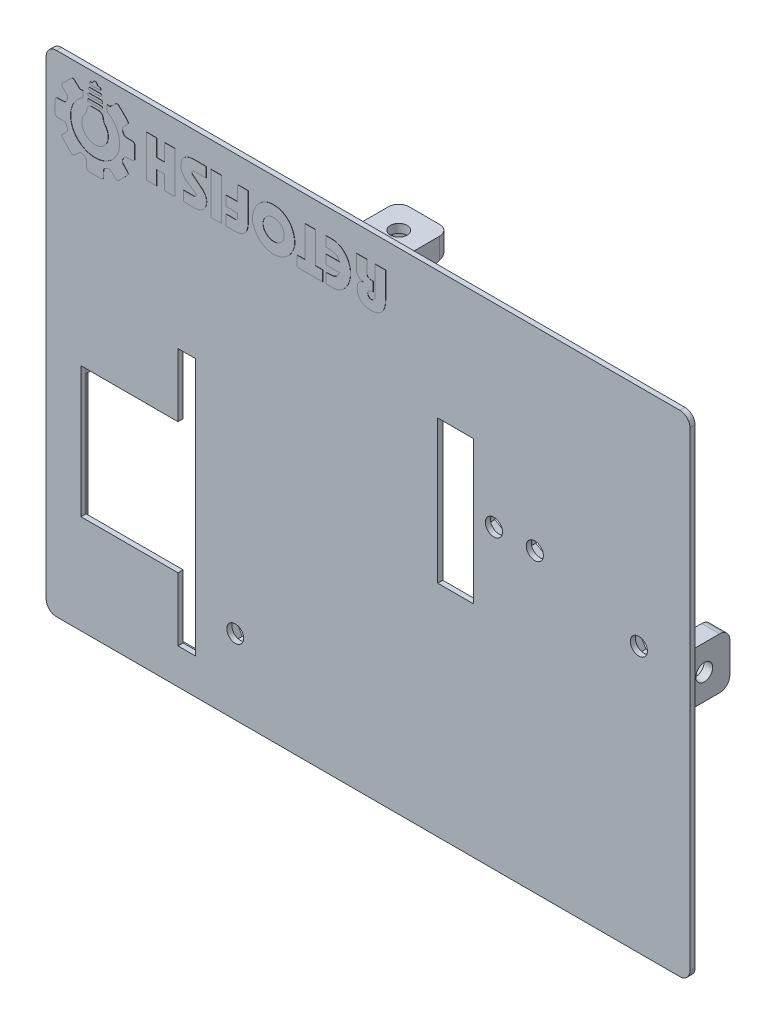
SolidWorks part; units mm, degrees
ref_plane "Front Plane" through (0, 0, 0) normal (0, 0, 1) x (1, 0, 0)
ref_plane "Top Plane" through (0, 0, 0) normal (0, 1, 0) x (1, 0, 0)
ref_plane "Right Plane" through (0, 0, 0) normal (1, 0, 0) x (0, 0, -1)
sketch "Sketch1" plane through (0, 0, 0) normal (0, 0, 1) x (1, 0, 0)
  line L1 (63, -48) -> (-63, -48)
  line L2 (63, -48) -> (63, 48)
  line L3 (63, 48) -> (-63, 48)
  line L4 (-63, -48) -> (-63, 48)
  line L5 (63, -48) -> (-63, 48) construction
  line L6 (63, 48) -> (-63, -48) construction
  circle A1 centre (53, 4) radius 1.675
  point P0 (0, 0)
  point P9 (0, 0)
  point P14 (0, 0)
  dimension "D4" = 52
  dimension "D3" = 10
  dimension "D1" = 126
  dimension "D2" = 96
extrude "Boss-Extrude1" add sketch "Sketch1" along normal blind 1
sketch "Sketch2" plane through (0, 0, 0) normal (0, 0, -1) x (-1, 0, 0)
  line L0 (-63, 48) -> (63, 48) construction
  line L1 (-59.8, 34.8) -> (-57.7, 34.8)
  line L2 (-59.8, 34.8) -> (-59.8, 44.8)
  line L3 (-59.8, 44.8) -> (-57.7, 44.8)
  line L4 (-57.7, 34.8) -> (-57.7, 44.8)
  line L5 (-59.8, 34.8) -> (-57.7, 44.8) construction
  line L6 (-59.8, 44.8) -> (-57.7, 34.8) construction
  line L7 (57.7, 34.8) -> (59.8, 34.8)
  line L8 (57.7, 34.8) -> (57.7, 44.8)
  line L9 (57.7, 44.8) -> (59.8, 44.8)
  line L10 (59.8, 34.8) -> (59.8, 44.8)
  line L11 (57.7, 34.8) -> (59.8, 44.8) construction
  line L12 (57.7, 44.8) -> (59.8, 34.8) construction
  line L13 (63, 48) -> (63, -48) construction
  line L14 (-63, -48) -> (-63, 48) construction
  line L15 (-59.8, -44.8) -> (-57.7, -44.8)
  line L16 (-59.8, -44.8) -> (-59.8, -34.8)
  line L17 (-59.8, -34.8) -> (-57.7, -34.8)
  line L18 (-57.7, -44.8) -> (-57.7, -34.8)
  line L19 (-59.8, -44.8) -> (-57.7, -34.8) construction
  line L20 (-59.8, -34.8) -> (-57.7, -44.8) construction
  line L21 (57.7, -44.8) -> (59.8, -44.8)
  line L22 (57.7, -44.8) -> (57.7, -34.8)
  line L23 (57.7, -34.8) -> (59.8, -34.8)
  line L24 (59.8, -44.8) -> (59.8, -34.8)
  line L25 (57.7, -44.8) -> (59.8, -34.8) construction
  line L26 (57.7, -34.8) -> (59.8, -44.8) construction
  line L27 (63, -48) -> (-63, -48) construction
  point P0 (-58.75, 39.8)
  point P5 (58.75, 39.8)
  point P12 (-58.75, -39.8)
  point P16 (0, 0)
  point P23 (58.75, -39.8)
  dimension "D1" = 2.1
  dimension "D3" = 10
  dimension "D4" = 10
  dimension "D5" = 3.2
  dimension "D6" = 3.2
  dimension "D7" = 3.2
  dimension "D8" = 3.2
  dimension "D11" = 10
  dimension "D12" = 10
  dimension "D13" = 3.2
  dimension "D14" = 3.2
  dimension "D15" = 3.2
  dimension "D16" = 3.2
extrude "Boss-Extrude2" add sketch "Sketch2" along normal blind 2.1 contours L1 L4 L2 | L4 L3 L2 | L10 L9 L8 | L7 L10 L8 | L15 L18 L17 L16 | L21 L24 L23 L22 region at (58.75, 39.8, 0) region at (-58.75, 39.8, 0)
chamfer "Chamfer1" distance 2 angle 45 4 edges at (57.7, 39.8, 0) (-57.7, 39.8, 0) (-57.7, -39.8, 0) (57.7, -39.8, 0)
sketch "Sketch7" plane through (0, 0, 1) normal (0, 0, 1) x (1, 0, 0)
  line L0 (63, -48) -> (63, 48) construction
  line L3 (63, 48) -> (-63, 48) construction
  circle A0 centre (32.63, 10) radius 1.675
  circle A1 centre (24.63, 10) radius 1.675
  dimension "D1" = 8
  dimension "D2" = 30.37
  dimension "D3" = 38
  dimension "3.3" = 3.35
extrude "Cut-Extrude5" cut sketch "Sketch7" against normal blind 10
sketch "Sketch9" plane through (0, 0, 1) normal (0, 0, 1) x (1, 0, 0)
  line L0 (63, 48) -> (-63, 48) construction
  line L1 (20.63, -5) -> (13.63, -5)
  line L2 (20.63, -5) -> (20.63, 23)
  line L3 (20.63, 23) -> (13.63, 23)
  line L4 (13.63, -5) -> (13.63, 23)
  line L5 (20.63, -5) -> (13.63, 23) construction
  line L6 (20.63, 23) -> (13.63, -5) construction
  line L8 (63, -48) -> (63, 48) construction
  point P0 (17.13, 9)
  dimension "D1" = 25
  dimension "D2" = 42.37
  dimension "D3" = 7
  dimension "D4" = 28
extrude "Cut-Extrude7" cut sketch "Sketch9" against normal blind 10
sketch "Sketch11" plane through (0, 0, 1) normal (0, 0, 1) x (1, 0, 0)
  line L1 (-63, -48) -> (63, -48) construction
  line L2 (63, -48) -> (63, 48) construction
  line L4 (-17, -20.2) -> (-8, -20.2)
  line L5 (-17, -20.2) -> (-17, -26.2)
  line L6 (-17, -26.2) -> (-8, -26.2)
  line L7 (-8, -20.2) -> (-8, -26.2)
  circle A1 centre (22, -36.45) radius 1.675
  circle A2 centre (22, -22.45) radius 1.675
  dimension "D1" = 9
  dimension "D2" = 6
  dimension "D3" = 71
  dimension "D4" = 41
  dimension "D5" = 11.55
  dimension "D8" = 41
  dimension "D9" = 3.35
  dimension "D10" = 14
  dimension "D7" = 27.8
extrude "Cut-Extrude8" cut sketch "Sketch11" against normal blind 10
sketch "Sketch21" plane through (0, 0, 0) normal (0, 0, -1) x (-1, 0, 0)
  line L7 (-50.7195, 7.95) -> (-55.2805, 7.95)
  line L8 (-55.2805, 7.95) -> (-57.5611, 4)
  line L9 (-57.5611, 4) -> (-55.2805, 0.05)
  line L10 (-55.2805, 0.05) -> (-50.7195, 0.05)
  line L11 (-50.7195, 0.05) -> (-48.4389, 4)
  line L12 (-48.4389, 4) -> (-50.7195, 7.95)
  line L13 (-51.3979, 6.775) -> (-54.6021, 6.775)
  line L14 (-54.6021, 6.775) -> (-56.2043, 4)
  line L15 (-56.2043, 4) -> (-54.6021, 1.225)
  line L16 (-54.6021, 1.225) -> (-51.3979, 1.225)
  line L17 (-51.3979, 1.225) -> (-49.7957, 4)
  line L18 (-49.7957, 4) -> (-51.3979, 6.775)
  line L25 (-21.83, 11.6166) -> (-24.63, 13.2332)
  line L26 (-24.63, 13.2332) -> (-27.43, 11.6166)
  line L27 (-27.43, 11.6166) -> (-27.43, 8.3834)
  line L28 (-27.43, 8.3834) -> (-24.63, 6.7668)
  line L29 (-24.63, 6.7668) -> (-21.83, 8.3834)
  line L30 (-21.83, 8.3834) -> (-21.83, 11.6166)
  line L31 (-20.68, 12.2805) -> (-24.63, 14.5611)
  line L32 (-24.63, 14.5611) -> (-28.58, 12.2805)
  line L33 (-28.58, 12.2805) -> (-28.58, 7.7195)
  line L34 (-28.58, 7.7195) -> (-24.63, 5.4389)
  line L35 (-24.63, 5.4389) -> (-20.68, 7.7195)
  line L36 (-20.68, 7.7195) -> (-20.68, 12.2805)
  line L37 (-29.83, 11.6166) -> (-32.63, 13.2332)
  line L38 (-32.63, 13.2332) -> (-35.43, 11.6166)
  line L39 (-35.43, 11.6166) -> (-35.43, 8.3834)
  line L40 (-35.43, 8.3834) -> (-32.63, 6.7668)
  line L41 (-32.63, 6.7668) -> (-29.83, 8.3834)
  line L42 (-29.83, 8.3834) -> (-29.83, 11.6166)
  line L43 (-28.68, 12.2805) -> (-32.63, 14.5611)
  line L44 (-32.63, 14.5611) -> (-36.58, 12.2805)
  line L45 (-36.58, 12.2805) -> (-36.58, 7.7195)
  line L46 (-36.58, 7.7195) -> (-32.63, 5.4389)
  line L47 (-32.63, 5.4389) -> (-28.68, 7.7195)
  line L48 (-28.68, 7.7195) -> (-28.68, 12.2805)
  line L76 (-63, 48) -> (63, 48) construction
  circle A1 centre (-53, 4) radius 3.95 construction
  circle A2 centre (-53, 4) radius 2.775 construction
  circle A4 centre (-24.63, 10) radius 2.8 construction
  circle A5 centre (-24.63, 10) radius 3.95 construction
  circle A6 centre (-32.63, 10) radius 2.8 construction
  circle A7 centre (-32.63, 10) radius 3.95 construction
  dimension "D1" = 5.6
  dimension "D2" = 7.9
extrude "Boss-Extrude3" add sketch "Sketch21" along normal blind 2
sketch "Sketch24" plane through (0, 0, 1) normal (0, 0, 1) x (1, 0, 0)
  line L0 (-63, 48) -> (-63, -48) construction
  line L1 (-56.2, -3.05) -> (-37.2, -3.05)
  line L2 (-56.2, -3.05) -> (-56.2, -28.65)
  line L3 (-56.2, -28.65) -> (-37.2, -28.65)
  line L4 (-37.2, -3.05) -> (-37.2, -28.65)
  line L5 (-56.2, -3.05) -> (-37.2, -28.65) construction
  line L6 (-56.2, -28.65) -> (-37.2, -3.05) construction
  line L11 (63, 48) -> (-63, 48) construction
  line L12 (-33.8, -41.05) -> (-37.2, -41.05)
  line L13 (-33.8, -41.05) -> (-33.8, 9.35)
  line L14 (-33.8, 9.35) -> (-37.2, 9.35)
  line L15 (-37.2, -41.05) -> (-37.2, 9.35)
  line L16 (-33.8, -41.05) -> (-37.2, 9.35) construction
  line L17 (-33.8, 9.35) -> (-37.2, -41.05) construction
  line L18 (-63, -48) -> (63, -48) construction
  circle A0 centre (-26, -33.35) radius 1.65
  point P0 (-46.7, -15.85)
  point P5 (-35.5, -15.85)
  dimension "D7" = 14.65
  dimension "D8" = 37
  dimension "D9" = 3.3
  dimension "D1" = 25.6
  dimension "D2" = 25.8
  dimension "D3" = 6.8
  dimension "D4" = 3.4
  dimension "D5" = 50.4
  dimension "D6" = 63.85
extrude "Cut-Extrude17" cut sketch "Sketch24" against normal blind 2 contours L4 L1 L2 L3 | L15 L12 L13 L14 L4 | A0 region at (-46.7, -15.85, 1) region at (-35.5, -15.85, 1) region at (-26, -33.35, 1)
sketch "Sketch26" plane through (0, 0, 0) normal (0, 0, -1) x (-1, 0, 0)
  line L0 (33.8, -28.2) -> (-57.8, -28.2)
  line L5 (-13.63, 23) -> (-13.63, -5) construction
  line L7 (33.8, -28.2) -> (33.8, -26.2)
  line L8 (-57.8, -28.2) -> (-57.8, -26.2)
  line L9 (33.8, -26.2) -> (-57.8, -26.2)
  line L10 (33.8, -41.05) -> (33.8, 9.35) construction
  line L11 (-6.63, -44.8) -> (-6.63, 45)
  line L12 (-6.63, -44.8) -> (-8.63, -44.8)
  line L13 (-6.63, 45) -> (-8.63, 45)
  line L14 (-8.63, -44.8) -> (-8.63, 45)
  line L15 (-57.8, -34.8) -> (-57.8, 34.8)
  line L16 (-57.8, -34.8) -> (-59.8, -34.8)
  line L17 (-57.8, 34.8) -> (-59.8, 34.8)
  line L18 (-59.8, -34.8) -> (-59.8, 34.8)
  line L19 (57.8, -34.8) -> (57.8, 34.8)
  line L20 (57.8, -34.8) -> (59.8, -34.8)
  line L21 (57.8, 34.8) -> (59.8, 34.8)
  line L22 (59.8, -34.8) -> (59.8, 34.8)
  line L23 (59.8, 43) -> (-59.8, 43)
  line L24 (59.8, 43) -> (59.8, 45)
  line L25 (-59.8, 43) -> (-59.8, 45)
  line L26 (59.8, 45) -> (-59.8, 45)
  line L31 (-57.8, -27.2) -> (33.8, -27.2) construction
  line L32 (17, -26.2) -> (8, -26.2) construction
  line L33 (-59.8, 34.8) -> (-55.7, 34.8) construction
  line L34 (-59.8, -34.8) -> (-55.7, -34.8) construction
  line L35 (-20.63, 23) -> (-13.63, 23) construction
  line L37 (59.8, 34.8) -> (59.8, 44.8) construction
  line L38 (57.8, 25) -> (-57.8, 25)
  line L39 (55.7, -34.8) -> (59.8, -34.8) construction
  line L40 (55.7, 34.8) -> (59.8, 34.8) construction
  line L43 (57.8, 25) -> (57.8, 23)
  line L44 (57.8, 23) -> (-57.8, 23)
  line L45 (-57.8, 25) -> (-57.8, 23)
  line L46 (57.7, -44.8) -> (-57.7, -44.8)
  line L47 (57.7, -44.8) -> (57.7, -42.8)
  line L48 (-57.7, -44.8) -> (-57.7, -42.8)
  line L49 (57.7, -42.8) -> (-57.7, -42.8)
  line L56 (-59.8, 34.8) -> (-59.8, 44.8) construction
  line L57 (-63, 48) -> (63, 48) construction
  line L58 (-59.8, -44.8) -> (-55.7, -44.8) construction
  line L59 (59.8, -44.8) -> (59.8, -34.8) construction
  line L60 (-57.7, -44.8) -> (-57.7, -34.8) construction
  line L61 (57.7, -34.8) -> (57.7, -44.8) construction
  point P0 (18, 0)
  dimension "D2" = 2
  dimension "D3" = 2
  dimension "D4" = 2
  dimension "D5" = 2
  dimension "D6" = 2
  dimension "D7" = 5
  dimension "D9" = 2
  dimension "D10" = 2
  dimension "D15" = 3
extrude "Boss-Extrude10" add sketch "Sketch26" along normal blind 2 contours L18 L16 L15 L8 L17 | L19 | L44 L38 L11 | L44 L14 L38 L15 | L0 L8 L9 L7 | L23 L25 L26 L24 | L46 L48 L49 L47 | L22 L21 L19 L20 | L14 L13 L11 L12 region at (58.8, 0, 0) region at (-25.585, 24, 0) region at (33.215, 24, 0)
fillet "Fillet2" radius 2 4 edges at (63, -48, 0.5) (63, 48, 0.5) (-63, 48, 0.5) (-63, -48, 0.5)
sketch "Sketch27" plane through (0, 0, 1) normal (0, 0, 1) x (1, 0, 0)
  line L1 (-20.9274, -16.1259) -> (30.4399, -16.1259)
  line L2 (-20.9274, -16.1259) -> (-20.9274, -40.4054)
  line L3 (-20.9274, -40.4054) -> (30.4399, -40.4054)
  line L4 (30.4399, -16.1259) -> (30.4399, -40.4054)
extrude "Boss-Extrude11" add sketch "Sketch27" against normal up to surface (1 mm away) up to face at (-24.35, -33.35, 0)
sketch "Sketch28" plane through (0, 0, 0) normal (0, 0, -1) x (-1, 0, 0)
  line L0 (-55.2805, 0.05) -> (-50.7195, 0.05) construction
  line L1 (27.6021, -30.575) -> (24.3979, -30.575)
  line L2 (24.3979, -30.575) -> (22.7957, -33.35)
  line L3 (22.7957, -33.35) -> (24.3979, -36.125)
  line L4 (24.3979, -36.125) -> (27.6021, -36.125)
  line L5 (27.6021, -36.125) -> (29.2043, -33.35)
  line L6 (29.2043, -33.35) -> (27.6021, -30.575)
  line L7 (28.2805, -29.4) -> (23.7195, -29.4)
  line L8 (23.7195, -29.4) -> (21.4389, -33.35)
  line L9 (21.4389, -33.35) -> (23.7195, -37.3)
  line L10 (23.7195, -37.3) -> (28.2805, -37.3)
  line L11 (28.2805, -37.3) -> (30.5611, -33.35)
  line L12 (30.5611, -33.35) -> (28.2805, -29.4)
  line L13 (-51.3979, 6.775) -> (-54.6021, 6.775) construction
  line L14 (-50.7195, 7.95) -> (-55.2805, 7.95) construction
  circle A0 centre (26, -33.35) radius 2.775 construction
  circle A1 centre (26, -33.35) radius 3.95 construction
extrude "Boss-Extrude12" add sketch "Sketch28" along normal up to surface (2 mm away) up to face at (53, 4, -2)
sketch "Sketch29" plane through (0, 0, 1) normal (0, 0, 1) x (1, 0, 0)
  line L0 (-52.3355, 41.8994) -> (-52.504, 41.9799)
  line L1 (-52.504, 41.9799) -> (-53.386, 41.9799)
  line L2 (-53.386, 41.9799) -> (-54.268, 41.9799)
  line L3 (-54.268, 41.9799) -> (-54.4366, 41.8994)
  line L4 (-52.2055, 44.9577) -> (-52.2814, 45.0336)
  line L5 (-52.2814, 45.0336) -> (-53.3967, 45.0336)
  line L6 (-53.3967, 45.0336) -> (-54.5115, 45.0336)
  line L7 (-54.5115, 45.0336) -> (-54.5928, 44.9635)
  line L8 (-51.9921, 43.9252) -> (-52.0681, 44.0012)
  line L9 (-52.0681, 44.0012) -> (-53.3834, 44.0012)
  line L10 (-53.3834, 44.0012) -> (-54.6981, 44.0012)
  line L11 (-54.6981, 44.0012) -> (-54.7795, 43.9311)
  line L12 (-51.9921, 42.9308) -> (-52.0681, 43.0067)
  line L13 (-52.0681, 43.0067) -> (-53.3834, 43.0067)
  line L14 (-53.3834, 43.0067) -> (-54.6981, 43.0067)
  line L15 (-54.6981, 43.0067) -> (-54.7795, 42.9366)
  line L16 (-46.6367, 36.76) -> (-45.9154, 36.7731)
  line L17 (-45.9154, 36.7731) -> (-45.816, 36.8394)
  line L18 (-45.6546, 37.0326) -> (-45.5954, 37.1608)
  line L19 (-45.5954, 37.1608) -> (-45.5954, 38.4325)
  line L20 (-45.5954, 38.4325) -> (-45.5954, 39.701)
  line L21 (-45.5954, 39.701) -> (-45.6567, 39.8261)
  line L22 (-45.8187, 40.0177) -> (-45.9162, 40.0866)
  line L23 (-45.9162, 40.0866) -> (-46.6367, 40.0997)
  line L24 (-50.9879, 43.8567) -> (-51.042, 43.882)
  line L25 (-51.042, 43.882) -> (-51.042, 43.2945)
  line L26 (-60.1618, 40.1023) -> (-60.8831, 40.0867)
  line L27 (-60.8831, 40.0867) -> (-60.9779, 40.0226)
  line L28 (-61.1393, 39.8314) -> (-61.2033, 39.701)
  line L29 (-61.2033, 39.701) -> (-61.2033, 38.4325)
  line L30 (-61.2033, 38.4325) -> (-61.2033, 37.1608)
  line L31 (-61.2033, 37.1608) -> (-61.1441, 37.0326)
  line L32 (-60.9827, 36.8394) -> (-60.8833, 36.7731)
  line L33 (-60.8833, 36.7731) -> (-60.1619, 36.76)
  line L34 (-55.0692, 31.6539) -> (-55.0561, 30.9461)
  line L35 (-55.0561, 30.9461) -> (-54.9921, 30.8513)
  line L36 (-54.8009, 30.6899) -> (-54.6705, 30.6259)
  line L37 (-54.6705, 30.6259) -> (-53.402, 30.6286)
  line L38 (-46.6372, 36.7852) -> (-45.9233, 36.7982)
  line L39 (-45.9233, 36.7982) -> (-45.8302, 36.8602)
  line L40 (-45.6774, 37.0433) -> (-45.6206, 37.1663)
  line L41 (-45.6206, 37.1663) -> (-45.6206, 38.4325)
  line L42 (-45.6206, 38.4325) -> (-45.6206, 39.6951)
  line L43 (-45.6206, 39.6951) -> (-45.6793, 39.8149)
  line L44 (-45.8329, 39.9969) -> (-45.9244, 40.0616)
  line L45 (-45.9244, 40.0616) -> (-46.6372, 40.0745)
  line L46 (-50.9984, 43.8337) -> (-51.0168, 43.8423)
  line L47 (-51.0168, 43.8423) -> (-51.0168, 43.2945)
  line L48 (-60.1612, 40.0771) -> (-60.8751, 40.0616)
  line L49 (-60.8751, 40.0616) -> (-60.9638, 40.0017)
  line L50 (-61.1167, 39.8202) -> (-61.1781, 39.6951)
  line L51 (-61.1781, 39.6951) -> (-61.1781, 38.4325)
  line L52 (-61.1781, 38.4325) -> (-61.1781, 37.1663)
  line L53 (-61.1781, 37.1663) -> (-61.1213, 37.0433)
  line L54 (-60.9685, 36.8602) -> (-60.8755, 36.7982)
  line L55 (-60.8755, 36.7982) -> (-60.1614, 36.7852)
  line L56 (-55.044, 31.6544) -> (-55.0311, 30.954)
  line L57 (-55.0311, 30.954) -> (-54.9713, 30.8654)
  line L58 (-54.7897, 30.7125) -> (-54.6647, 30.6512)
  line L59 (-54.6647, 30.6512) -> (-53.402, 30.6538)
  line L60 (-52.3464, 41.8767) -> (-52.5097, 41.9547)
  line L61 (-52.5097, 41.9547) -> (-53.386, 41.9547)
  line L62 (-53.386, 41.9547) -> (-54.2623, 41.9547)
  line L63 (-54.2623, 41.9547) -> (-54.4258, 41.8766)
  line L64 (-52.01, 42.913) -> (-52.0785, 42.9815)
  line L65 (-52.0785, 42.9815) -> (-53.3834, 42.9815)
  line L66 (-53.3834, 42.9815) -> (-54.6888, 42.9815)
  line L67 (-54.6888, 42.9815) -> (-54.7629, 42.9177)
  line L68 (-52.01, 43.9074) -> (-52.0785, 43.976)
  line L69 (-52.0785, 43.976) -> (-53.3834, 43.976)
  line L70 (-53.3834, 43.976) -> (-54.6888, 43.976)
  line L71 (-54.6888, 43.976) -> (-54.7629, 43.9122)
  line L72 (-52.2233, 44.9399) -> (-52.2919, 45.0084)
  line L73 (-52.2919, 45.0084) -> (-53.3967, 45.0084)
  line L74 (-53.3967, 45.0084) -> (-54.5021, 45.0084)
  line L75 (-54.5021, 45.0084) -> (-54.5762, 44.9446)
  spline S0 degree 3 poles (-54.4366, 41.8994) (-54.5178, 41.8612) (-54.6782, 41.7629) (-54.8392, 41.5798) (-54.9479, 41.3528) (-54.9858, 41.1456) (-54.9947, 41.0469) knots -0.000046 -0.000046 -0.000046 -0.000046 0.249973 0.499993 0.750012 1.000031 1.000031 1.000031 1.000031
  spline S1 degree 3 poles (-54.9947, 41.0469) (-55.0032, 40.9545) (-55.0291, 40.7611) (-55.1072, 40.5332) (-55.2273, 40.3283) (-55.361, 40.142) (-55.4505, 40.0264) (-55.4934, 39.9722) knots -0.000035 -0.000035 -0.000035 -0.000035 0.249965 0.499966 0.749966 0.874966 0.999966 0.999966 0.999966 0.999966
  spline S2 degree 3 poles (-55.4934, 39.9722) (-55.538, 39.9153) (-55.6187, 39.7997) (-55.7343, 39.5948) (-55.8344, 39.3728) (-55.89, 39.2147) (-55.9141, 39.1353) knots 0.000077 0.000077 0.000077 0.000077 0.250072 0.500067 0.750063 1.000058 1.000058 1.000058 1.000058
  spline S3 degree 3 poles (-55.9141, 39.1353) (-55.9285, 39.0882) (-55.9587, 38.9859) (-55.9771, 38.8769) (-55.9846, 38.7369) (-55.9864, 38.58) (-55.9866, 38.4682) (-55.9866, 38.4165) knots -0.00008 -0.00008 -0.00008 -0.00008 0.24994 0.49996 0.74998 0.87499 1 1 1 1
  spline S4 degree 3 poles (-55.9866, 38.4165) (-55.9866, 38.365) (-55.9864, 38.2539) (-55.9846, 38.097) (-55.9774, 37.9566) (-55.9595, 37.8475) (-55.9307, 37.7488) (-55.9168, 37.7032) knots 0 0 0 0 0.124986 0.249972 0.499943 0.749915 0.999887 0.999887 0.999887 0.999887
  spline S5 degree 3 poles (-55.9168, 37.7032) (-55.8938, 37.6287) (-55.8418, 37.4865) (-55.737, 37.2529) (-55.6166, 37.0315) (-55.5412, 36.9154) (-55.4978, 36.857) knots 0.000095 0.000095 0.000095 0.000095 0.250106 0.500117 0.750127 1.000138 1.000138 1.000138 1.000138
  spline S6 degree 3 poles (-55.4978, 36.857) (-55.3586, 36.6681) (-55.0234, 36.3271) (-54.4128, 35.9767) (-53.7294, 35.793) (-53.2424, 35.7953) (-53.0064, 35.8287) knots -0.000037 -0.000037 -0.000037 -0.000037 0.24997 0.499977 0.749983 0.99999 0.99999 0.99999 0.99999
  spline S7 degree 3 poles (-53.0064, 35.8287) (-52.8309, 35.8538) (-52.4882, 35.9451) (-51.9971, 36.1935) (-51.5619, 36.5368) (-51.3262, 36.8159) (-51.2251, 36.9669) knots 0.000014 0.000014 0.000014 0.000014 0.24999 0.499967 0.749943 0.99992 0.99992 0.99992 0.99992
  spline S8 degree 3 poles (-51.2251, 36.9669) (-51.1872, 37.0244) (-51.1114, 37.1455) (-51.0271, 37.3088) (-50.9543, 37.4835) (-50.9041, 37.636) (-50.8819, 37.7086) knots 0.000188 0.000188 0.000188 0.000188 0.250177 0.500166 0.750155 1.000144 1.000144 1.000144 1.000144
  spline S9 degree 3 poles (-50.8819, 37.7086) (-50.8679, 37.7533) (-50.8392, 37.8497) (-50.8213, 37.9582) (-50.8141, 38.0983) (-50.8123, 38.2547) (-50.8121, 38.3653) (-50.8121, 38.4165) knots -0.000217 -0.000217 -0.000217 -0.000217 0.249837 0.499891 0.749946 0.874973 1 1 1 1
  spline S10 degree 3 poles (-50.8121, 38.4165) (-50.8121, 38.4683) (-50.8123, 38.58) (-50.8141, 38.7373) (-50.8213, 38.8777) (-50.8392, 38.9867) (-50.868, 39.0865) (-50.8819, 39.1325) knots 0 0 0 0 0.124966 0.249933 0.499865 0.749798 0.99973 0.99973 0.99973 0.99973
  spline S11 degree 3 poles (-50.8819, 39.1325) (-50.9067, 39.2125) (-50.9636, 39.3635) (-51.0811, 39.6169) (-51.2158, 39.854) (-51.2932, 39.9675) (-51.3397, 40.0252) knots 0.00022 0.00022 0.00022 0.00022 0.250216 0.500211 0.750207 1.000202 1.000202 1.000202 1.000202
  spline S12 degree 3 poles (-51.3397, 40.0252) (-51.3766, 40.0714) (-51.4527, 40.1694) (-51.5691, 40.3342) (-51.6756, 40.5236) (-51.7359, 40.7185) (-51.7653, 40.8923) (-51.7759, 40.9952) (-51.7801, 41.0448) knots -0.000102 -0.000102 -0.000102 -0.000102 0.124929 0.24996 0.500021 0.750083 0.875114 1.000144 1.000144 1.000144 1.000144
  spline S13 degree 3 poles (-51.7801, 41.0448) (-51.7835, 41.0901) (-51.7927, 41.1891) (-51.8096, 41.2858) (-51.8326, 41.3664) (-51.8558, 41.4196) (-51.8684, 41.4454) knots -0.000267 -0.000267 -0.000267 -0.000267 0.249732 0.499731 0.74973 0.999729 0.999729 0.999729 0.999729
  spline S14 degree 3 poles (-51.8684, 41.4454) (-51.8925, 41.4941) (-51.9493, 41.5872) (-52.0584, 41.7123) (-52.1874, 41.8187) (-52.285, 41.8754) (-52.3355, 41.8994) knots 0.000158 0.000158 0.000158 0.000158 0.250127 0.500096 0.750065 1.000034 1.000034 1.000034 1.000034
  spline S15 degree 3 poles (-52.3739, 45.5372) (-52.3563, 45.5477) (-52.3219, 45.5729) (-52.2885, 45.619) (-52.2668, 45.6759) (-52.2608, 45.7318) (-52.2603, 45.7577) knots 0.006401 0.006401 0.006401 0.006401 0.255102 0.503803 0.752504 1.001206 1.001206 1.001206 1.001206
  spline S16 degree 3 poles (-52.2603, 45.7577) (-52.2592, 45.7835) (-52.2602, 45.8407) (-52.2745, 45.8939) (-52.2999, 45.9404) (-52.3359, 45.9778) (-52.3535, 45.9938) knots -0.001199 -0.001199 -0.001199 -0.001199 0.249371 0.499941 0.750511 1.001081 1.001081 1.001081 1.001081
  spline S17 degree 3 poles (-52.3535, 45.9938) (-52.3614, 46.0012) (-52.3767, 46.0127) (-52.4208, 46.0275) (-52.4932, 46.0387) (-52.5833, 46.0449) (-52.6232, 46.0471) knots -0.001587 -0.001587 -0.001587 -0.001587 0.248739 0.499065 0.749392 0.999718 0.999718 0.999718 0.999718
  spline S18 degree 3 poles (-52.6232, 46.0471) (-52.6677, 46.0493) (-52.7708, 46.0557) (-52.8404, 46.0643) (-52.9073, 46.097) (-52.9205, 46.1368) (-52.9238, 46.1566) knots 0.000245 0.000245 0.000245 0.000245 0.251684 0.503123 0.754563 1.006002 1.006002 1.006002 1.006002
  spline S19 degree 3 poles (-52.9238, 46.1566) (-52.9276, 46.1843) (-52.9376, 46.2464) (-52.9548, 46.2965) (-52.9791, 46.3398) (-53.015, 46.3818) (-53.0317, 46.4001) knots -0.001538 -0.001538 -0.001538 -0.001538 0.249242 0.500023 0.750803 1.001583 1.001583 1.001583 1.001583
  spline S20 degree 3 poles (-53.0317, 46.4001) (-53.0783, 46.454) (-53.1992, 46.5492) (-53.386, 46.5881) (-53.5728, 46.5492) (-53.6937, 46.454) (-53.7404, 46.4001) knots -0.000592 -0.000592 -0.000592 -0.000592 0.249704 0.5 0.750296 1.000592 1.000592 1.000592 1.000592
  spline S21 degree 3 poles (-53.7404, 46.4001) (-53.7571, 46.3818) (-53.793, 46.3398) (-53.8172, 46.2965) (-53.8344, 46.2464) (-53.8444, 46.1843) (-53.8483, 46.1566) knots -0.001583 -0.001583 -0.001583 -0.001583 0.249198 0.499979 0.75076 1.001541 1.001541 1.001541 1.001541
  spline S22 degree 3 poles (-53.8483, 46.1566) (-53.8516, 46.1364) (-53.8668, 46.0954) (-53.9322, 46.0655) (-53.9988, 46.0582) (-54.0793, 46.052) (-54.1357, 46.0487) (-54.1619, 46.0472) knots -0.006038 -0.006038 -0.006038 -0.006038 0.245488 0.497014 0.748539 0.874302 1.000065 1.000065 1.000065 1.000065
  spline S23 degree 3 poles (-54.1619, 46.0472) (-54.1886, 46.0457) (-54.2462, 46.0423) (-54.3264, 46.0363) (-54.3891, 46.0261) (-54.4242, 46.0112) (-54.4551, 45.9834) (-54.4685, 45.9705) knots -0.000062 -0.000062 -0.000062 -0.000062 0.124957 0.249976 0.500015 0.750053 1.000092 1.000092 1.000092 1.000092
  spline S24 degree 3 poles (-54.4685, 45.9705) (-54.4816, 45.9579) (-54.5105, 45.9278) (-54.5251, 45.9009) (-54.5341, 45.8694) (-54.5358, 45.8219) (-54.5358, 45.8014) knots -0.000104 -0.000104 -0.000104 -0.000104 0.249922 0.499948 0.749974 1 1 1 1
  spline S25 degree 3 poles (-54.5358, 45.8014) (-54.5358, 45.768) (-54.5308, 45.6952) (-54.509, 45.6234) (-54.4764, 45.572) (-54.4452, 45.5494) (-54.4285, 45.5403) knots 0 0 0 0 0.249288 0.498577 0.747865 0.997153 0.997153 0.997153 0.997153
  spline S26 degree 3 poles (-54.4285, 45.5403) (-54.4142, 45.5369) (-54.3939, 45.5338) (-54.2812, 45.5235) (-54.08, 45.5149) (-53.7611, 45.5078) (-53.4065, 45.5051) (-53.0511, 45.5066) (-52.7314, 45.5125) (-52.5254, 45.5209) (-52.4142, 45.5301) (-52.3897, 45.5337) (-52.3739, 45.5372) knots 0.023161 0.023161 0.023161 0.023161 0.0824 0.14164 0.260119 0.378598 0.497077 0.615557 0.734036 0.852515 0.911754 0.970994 0.970994 0.970994 0.970994
  spline S27 degree 3 poles (-54.5928, 44.9635) (-54.6083, 44.9496) (-54.6438, 44.9155) (-54.6588, 44.8898) (-54.6677, 44.8609) (-54.6691, 44.8096) (-54.6691, 44.788) knots 0.001503 0.001503 0.001503 0.001503 0.251127 0.500751 0.750376 1 1 1 1
  spline S28 degree 3 poles (-54.6691, 44.788) (-54.6691, 44.771) (-54.6675, 44.7377) (-54.6613, 44.6834) (-54.651, 44.6356) (-54.6464, 44.6212) (-54.6421, 44.6125) knots 0 0 0 0 0.2514 0.5028 0.7542 1.0056 1.0056 1.0056 1.0056
  spline S29 degree 3 poles (-54.6421, 44.6125) (-54.6357, 44.5988) (-54.6209, 44.5678) (-54.6009, 44.5477) (-54.5631, 44.5294) (-54.4732, 44.5123) (-54.3268, 44.502) (-54.1108, 44.4964) (-53.8592, 44.4948) (-53.6136, 44.4944) (-53.4651, 44.4943) (-53.3941, 44.4943) knots -0.00138 -0.00138 -0.00138 -0.00138 0.123789 0.248959 0.374128 0.499298 0.624468 0.749637 0.874807 0.937392 0.999976 0.999976 0.999976 0.999976
  spline S30 degree 3 poles (-53.3941, 44.4943) (-53.311, 44.4946) (-53.1373, 44.4954) (-52.8506, 44.4976) (-52.5617, 44.5018) (-52.3741, 44.5084) (-52.2812, 44.5155) (-52.2613, 44.5184) (-52.2483, 44.5211) knots 0.000038 0.000038 0.000038 0.000038 0.11625 0.232461 0.464885 0.697309 0.813521 0.929733 0.929733 0.929733 0.929733
  spline S31 degree 3 poles (-52.2483, 44.5211) (-52.2289, 44.5319) (-52.1897, 44.5586) (-52.156, 44.6048) (-52.1346, 44.6639) (-52.1296, 44.7291) (-52.1296, 44.7586) knots 0.001931 0.001931 0.001931 0.001931 0.251448 0.500965 0.750483 1 1 1 1
  spline S32 degree 3 poles (-52.1296, 44.7586) (-52.1296, 44.7833) (-52.131, 44.8412) (-52.1404, 44.8766) (-52.156, 44.9061) (-52.1903, 44.9425) (-52.2055, 44.9577) knots 0 0 0 0 0.25 0.5 0.75 1 1 1 1
  spline S33 degree 3 poles (-54.7795, 43.9311) (-54.795, 43.9171) (-54.8308, 43.8831) (-54.8454, 43.8581) (-54.8544, 43.8292) (-54.8558, 43.7755) (-54.8558, 43.7529) knots 0.001495 0.001495 0.001495 0.001495 0.251121 0.500747 0.750374 1 1 1 1
  spline S34 degree 3 poles (-54.8558, 43.7529) (-54.8558, 43.7209) (-54.8493, 43.6533) (-54.8226, 43.5759) (-54.7837, 43.5186) (-54.7531, 43.4967) (-54.7358, 43.4878) knots 0 0 0 0 0.247513 0.495027 0.74254 0.990053 0.990053 0.990053 0.990053
  spline S35 degree 3 poles (-54.7358, 43.4878) (-54.7172, 43.4848) (-54.6912, 43.4824) (-54.546, 43.4743) (-54.2818, 43.4677) (-53.8597, 43.4625) (-53.3886, 43.461) (-52.9171, 43.4628) (-52.4935, 43.4683) (-52.2271, 43.4753) (-52.08, 43.4838) (-52.0525, 43.4865) (-52.0332, 43.4896) knots 0.023969 0.023969 0.023969 0.023969 0.083123 0.142277 0.260585 0.378892 0.4972 0.615508 0.733816 0.852123 0.911277 0.970431 0.970431 0.970431 0.970431
  spline S36 degree 3 poles (-52.0332, 43.4896) (-52.0141, 43.5004) (-51.9757, 43.5268) (-51.9423, 43.573) (-51.9212, 43.6319) (-51.9162, 43.6968) (-51.9162, 43.7262) knots 0.007864 0.007864 0.007864 0.007864 0.255898 0.503932 0.751966 1 1 1 1
  spline S37 degree 3 poles (-51.9162, 43.7262) (-51.9162, 43.7509) (-51.9176, 43.8088) (-51.9271, 43.8441) (-51.9426, 43.8737) (-51.977, 43.9101) (-51.9921, 43.9252) knots 0 0 0 0 0.25 0.5 0.75 1 1 1 1
  spline S38 degree 3 poles (-54.7795, 42.9366) (-54.795, 42.9226) (-54.8308, 42.8886) (-54.8454, 42.8636) (-54.8544, 42.8348) (-54.8558, 42.781) (-54.8558, 42.7584) knots 0.001495 0.001495 0.001495 0.001495 0.251121 0.500747 0.750374 1 1 1 1
  spline S39 degree 3 poles (-54.8558, 42.7584) (-54.8558, 42.7253) (-54.85, 42.6543) (-54.8255, 42.5792) (-54.7893, 42.5254) (-54.7579, 42.5041) (-54.7407, 42.4958) knots 0 0 0 0 0.248876 0.497751 0.746627 0.995502 0.995502 0.995502 0.995502
  spline S40 degree 3 poles (-54.7407, 42.4958) (-54.7225, 42.4925) (-54.6973, 42.4901) (-54.5522, 42.4812) (-54.2878, 42.4739) (-53.8648, 42.468) (-53.3926, 42.4658) (-52.9197, 42.4673) (-52.4949, 42.4727) (-52.2277, 42.4799) (-52.0801, 42.4888) (-52.0528, 42.4916) (-52.0336, 42.4949) knots 0.022815 0.022815 0.022815 0.022815 0.082071 0.141327 0.25984 0.378353 0.496866 0.615379 0.733891 0.852404 0.911661 0.970917 0.970917 0.970917 0.970917
  spline S41 degree 3 poles (-52.0336, 42.4949) (-52.0145, 42.5057) (-51.9759, 42.5321) (-51.9424, 42.5784) (-51.9212, 42.6373) (-51.9162, 42.7023) (-51.9162, 42.7317) knots 0.006322 0.006322 0.006322 0.006322 0.254742 0.503161 0.751581 1 1 1 1
  spline S42 degree 3 poles (-51.9162, 42.7317) (-51.9162, 42.7564) (-51.9176, 42.8143) (-51.9271, 42.8496) (-51.9426, 42.8792) (-51.977, 42.9156) (-51.9921, 42.9308) knots 0 0 0 0 0.25 0.5 0.75 1 1 1 1
  spline S43 degree 3 poles (-45.816, 36.8394) (-45.7989, 36.8512) (-45.7655, 36.8771) (-45.7239, 36.9199) (-45.6874, 36.9694) (-45.6644, 37.0117) (-45.6546, 37.0326) knots 0.001432 0.001432 0.001432 0.001432 0.251178 0.500925 0.750671 1.000417 1.000417 1.000417 1.000417
  spline S44 degree 3 poles (-45.6567, 39.8261) (-45.6667, 39.8459) (-45.6889, 39.8842) (-45.7291, 39.9381) (-45.7739, 39.9846) (-45.8028, 40.0072) (-45.8187, 40.0177) knots -0.000393 -0.000393 -0.000393 -0.000393 0.25058 0.501554 0.752527 1.0035 1.0035 1.0035 1.0035
  spline S45 degree 3 poles (-46.6367, 40.0997) (-46.6857, 40.1006) (-46.788, 40.1026) (-46.9582, 40.1065) (-47.135, 40.1122) (-47.2937, 40.1229) (-47.453, 40.1457) (-47.5845, 40.2001) (-47.6632, 40.2896) (-47.7009, 40.3333) knots -0.000028 -0.000028 -0.000028 -0.000028 0.062487 0.125003 0.250033 0.375063 0.500093 0.750154 1.000215 1.000215 1.000215 1.000215
  spline S46 degree 3 poles (-47.7009, 40.3333) (-47.7372, 40.376) (-47.7911, 40.4619) (-47.8915, 40.6578) (-47.9748, 40.868) (-48.0079, 40.9786) (-48.0189, 41.0395) knots -0.000387 -0.000387 -0.000387 -0.000387 0.249492 0.499372 0.749252 0.999131 0.999131 0.999131 0.999131
  spline S47 degree 3 poles (-48.0189, 41.0395) (-48.0229, 41.06) (-48.0277, 41.1003) (-48.0293, 41.169) (-48.0254, 41.2386) (-48.0198, 41.2804) (-48.0161, 41.3017) knots 0.002368 0.002368 0.002368 0.002368 0.253295 0.504222 0.755148 1.006075 1.006075 1.006075 1.006075
  spline S48 degree 3 poles (-48.0161, 41.3017) (-48.0086, 41.3338) (-47.9907, 41.3924) (-47.9194, 41.4954) (-47.7958, 41.6298) (-47.6447, 41.7849) (-47.5356, 41.895) (-47.4851, 41.9458) knots -0.003933 -0.003933 -0.003933 -0.003933 0.247043 0.498019 0.748995 0.874483 0.99997 0.99997 0.99997 0.99997
  spline S49 degree 3 poles (-47.4851, 41.9458) (-47.4282, 42.0033) (-47.3068, 42.1271) (-47.1326, 42.3115) (-46.9866, 42.485) (-46.9133, 42.619) (-46.9029, 42.6944) (-46.9023, 42.7348) knots 0.000026 0.000026 0.000026 0.000026 0.124943 0.249859 0.499692 0.749525 0.999358 0.999358 0.999358 0.999358
  spline S50 degree 3 poles (-46.9023, 42.7348) (-46.9023, 42.7608) (-46.9028, 42.8172) (-46.9167, 42.8946) (-46.9703, 42.9923) (-47.1186, 43.1649) (-47.2853, 43.342) (-47.4815, 43.5424) (-47.6734, 43.7365) (-47.7895, 43.8536) (-47.8451, 43.9097) knots 0.000455 0.000455 0.000455 0.000455 0.125397 0.250339 0.500223 0.625165 0.750107 0.875049 0.93752 0.999991 0.999991 0.999991 0.999991
  spline S51 degree 3 poles (-47.8451, 43.9097) (-47.9607, 44.0259) (-48.2034, 44.2684) (-48.5049, 44.5649) (-48.6898, 44.7433) (-48.79, 44.8348) (-48.8043, 44.8478) (-48.8171, 44.857) knots 0.000018 0.000018 0.000018 0.000018 0.245051 0.490084 0.735118 0.857634 0.980151 0.980151 0.980151 0.980151
  spline S52 degree 3 poles (-48.8171, 44.857) (-48.8442, 44.8737) (-48.8996, 44.8967) (-49.0142, 44.9209) (-49.1326, 44.9231) (-49.1947, 44.9129) (-49.2262, 44.9026) knots -0.000665 -0.000665 -0.000665 -0.000665 0.249725 0.500115 0.750505 1.000894 1.000894 1.000894 1.000894
  spline S53 degree 3 poles (-49.2262, 44.9026) (-49.2481, 44.8958) (-49.2734, 44.8803) (-49.3894, 44.7906) (-49.5277, 44.6625) (-49.6709, 44.525) (-49.761, 44.4366) (-49.8036, 44.3947) knots -0.00133 -0.00133 -0.00133 -0.00133 0.249012 0.499355 0.749698 0.874869 1.000041 1.000041 1.000041 1.000041
  spline S54 degree 3 poles (-49.8036, 44.3947) (-49.8697, 44.3298) (-50.008, 44.1963) (-50.1879, 44.0282) (-50.3039, 43.9246) (-50.3696, 43.8713) (-50.3893, 43.8567) (-50.4021, 43.85) knots -0.000057 -0.000057 -0.000057 -0.000057 0.249885 0.499826 0.749767 0.874738 0.999708 0.999708 0.999708 0.999708
  spline S55 degree 3 poles (-50.4021, 43.85) (-50.4428, 43.8284) (-50.5292, 43.8023) (-50.6848, 43.7902) (-50.8452, 43.8076) (-50.9415, 43.8362) (-50.9879, 43.8567) knots 0.000147 0.000147 0.000147 0.000147 0.250375 0.500603 0.750831 1.001059 1.001059 1.001059 1.001059
  spline S56 degree 3 poles (-51.042, 43.2945) (-51.042, 43.2196) (-51.0423, 43.0628) (-51.0432, 42.8699) (-51.0446, 42.7103) (-51.0455, 42.6599) (-51.0463, 42.6278) knots 0 0 0 0 0.214168 0.428337 0.642505 0.856674 0.856674 0.856674 0.856674
  spline S57 degree 3 poles (-51.0463, 42.6278) (-51.031, 42.6153) (-51.004, 42.5938) (-50.9387, 42.5459) (-50.858, 42.4888) (-50.794, 42.445) (-50.763, 42.4242) knots 0.237673 0.237673 0.237673 0.237673 0.428232 0.618791 0.80935 0.999909 0.999909 0.999909 0.999909
  spline S58 degree 3 poles (-50.763, 42.4242) (-50.5356, 42.2722) (-50.0968, 41.9284) (-49.566, 41.3445) (-49.1426, 40.6827) (-48.9312, 40.1787) (-48.8469, 39.9232) knots 0.000017 0.000017 0.000017 0.000017 0.250009 0.500001 0.749994 0.999986 0.999986 0.999986 0.999986
  spline S59 degree 3 poles (-48.8469, 39.9232) (-48.7677, 39.6844) (-48.647, 39.1901) (-48.5679, 38.2018) (-48.7546, 36.9787) (-49.2968, 35.8668) (-49.9238, 35.0994) (-50.3039, 34.7616) (-50.5047, 34.6104) knots 0.000008 0.000008 0.000008 0.000008 0.125007 0.250007 0.500007 0.750006 0.875006 1.000005 1.000005 1.000005 1.000005
  spline S60 degree 3 poles (-50.5047, 34.6104) (-50.7009, 34.4631) (-51.1195, 34.1963) (-52.0012, 33.8081) (-53.1773, 33.5812) (-54.3695, 33.7078) (-55.2829, 34.0202) (-55.7243, 34.251) (-55.933, 34.3812) knots -0.000006 -0.000006 -0.000006 -0.000006 0.124995 0.249995 0.499996 0.749997 0.874997 0.999997 0.999997 0.999997 0.999997
  spline S61 degree 3 poles (-55.933, 34.3812) (-56.1608, 34.5232) (-56.5953, 34.8499) (-57.3184, 35.6188) (-57.9591, 36.7712) (-58.2024, 38.0686) (-58.1377, 39.1252) (-58.0122, 39.6566) (-57.9278, 39.9124) knots 0.000002 0.000002 0.000002 0.000002 0.125001 0.249999 0.499997 0.749994 0.874992 0.999991 0.999991 0.999991 0.999991
  spline S62 degree 3 poles (-57.9278, 39.9124) (-57.8447, 40.1664) (-57.6353, 40.6648) (-57.2116, 41.3319) (-56.6837, 41.9201) (-56.2603, 42.2567) (-56.0383, 42.4056) knots 0.000018 0.000018 0.000018 0.000018 0.250027 0.500036 0.750045 1.000054 1.000054 1.000054 1.000054
  spline S63 degree 3 poles (-56.0383, 42.4056) (-56.0078, 42.4257) (-55.9447, 42.4672) (-55.8626, 42.5203) (-55.7946, 42.5632) (-55.7649, 42.5807) (-55.7479, 42.5904) knots -0.000318 -0.000318 -0.000318 -0.000318 0.209989 0.420296 0.630603 0.84091 0.84091 0.84091 0.84091
  spline S64 degree 3 poles (-45.8302, 36.8602) (-45.8139, 36.8714) (-45.7821, 36.8962) (-45.7432, 36.9363) (-45.7089, 36.9827) (-45.6868, 37.0233) (-45.6774, 37.0433) knots 0.002323 0.002323 0.002323 0.002323 0.251742 0.501161 0.750581 1 1 1 1
  spline S65 degree 3 poles (-45.6793, 39.8149) (-45.6888, 39.8338) (-45.7101, 39.8705) (-45.7486, 39.922) (-45.7913, 39.9663) (-45.8181, 39.9871) (-45.8329, 39.9969) knots 0 0 0 0 0.25139 0.502779 0.754169 1.005559 1.005559 1.005559 1.005559
  spline S66 degree 3 poles (-46.6372, 40.0745) (-46.6862, 40.0754) (-46.7885, 40.0774) (-46.9589, 40.0813) (-47.1362, 40.087) (-47.2961, 40.0978) (-47.4586, 40.1208) (-47.6011, 40.1801) (-47.6811, 40.2717) (-47.72, 40.3169) knots -0.000034 -0.000034 -0.000034 -0.000034 0.062489 0.125013 0.250059 0.375105 0.500152 0.750245 1.000338 1.000338 1.000338 1.000338
  spline S67 degree 3 poles (-47.72, 40.3169) (-47.7374, 40.3372) (-47.767, 40.378) (-47.8327, 40.4856) (-47.9136, 40.6464) (-47.9986, 40.8591) (-48.0325, 40.9726) (-48.0436, 41.0348) knots -0.000527 -0.000527 -0.000527 -0.000527 0.124393 0.249313 0.499154 0.748994 0.998835 0.998835 0.998835 0.998835
  spline S68 degree 3 poles (-48.0436, 41.0348) (-48.0479, 41.0564) (-48.0529, 41.0992) (-48.0545, 41.1699) (-48.0505, 41.2414) (-48.0447, 41.2848) (-48.0408, 41.3068) knots 0.003226 0.003226 0.003226 0.003226 0.25457 0.505915 0.757259 1.008604 1.008604 1.008604 1.008604
  spline S69 degree 3 poles (-48.0408, 41.3068) (-48.0328, 41.3409) (-48.0138, 41.4034) (-47.9507, 41.4944) (-47.865, 41.5917) (-47.7771, 41.6851) (-47.6792, 41.7855) (-47.5855, 41.8804) (-47.5297, 41.9366) (-47.503, 41.9635) knots -0.005543 -0.005543 -0.005543 -0.005543 0.245831 0.497206 0.622893 0.74858 0.874267 0.937111 0.999954 0.999954 0.999954 0.999954
  spline S70 degree 3 poles (-47.503, 41.9635) (-47.4731, 41.9937) (-47.4114, 42.0564) (-47.3058, 42.165) (-47.1941, 42.2831) (-47.0929, 42.3976) (-46.9955, 42.5215) (-46.9374, 42.6277) (-46.928, 42.6974) (-46.9275, 42.7349) knots 0.000041 0.000041 0.000041 0.000041 0.062471 0.124902 0.249763 0.374624 0.499485 0.749207 0.998929 0.998929 0.998929 0.998929
  spline S71 degree 3 poles (-46.9275, 42.7349) (-46.9275, 42.7603) (-46.9281, 42.8165) (-46.9376, 42.8674) (-46.9646, 42.9298) (-47.0272, 43.0198) (-47.1372, 43.148) (-47.3036, 43.3246) (-47.4995, 43.5248) (-47.6913, 43.7188) (-47.8074, 43.8359) (-47.863, 43.8919) knots 0.000773 0.000773 0.000773 0.000773 0.125675 0.250576 0.375478 0.50038 0.625281 0.750183 0.875084 0.937535 0.999986 0.999986 0.999986 0.999986
  spline S72 degree 3 poles (-47.863, 43.8919) (-47.9781, 44.0077) (-48.22, 44.2494) (-48.4695, 44.4949) (-48.6323, 44.6527) (-48.731, 44.7466) (-48.7893, 44.8005) (-48.8221, 44.8289) (-48.8269, 44.833) (-48.8311, 44.836) knots 0.000027 0.000027 0.000027 0.000027 0.244111 0.488195 0.610236 0.732278 0.85432 0.915341 0.976362 0.976362 0.976362 0.976362
  spline S73 degree 3 poles (-48.8311, 44.836) (-48.8563, 44.8516) (-48.907, 44.8723) (-49.0179, 44.896) (-49.132, 44.8977) (-49.1892, 44.8882) (-49.2186, 44.8786) knots 0.002003 0.002003 0.002003 0.002003 0.251839 0.501675 0.751511 1.001347 1.001347 1.001347 1.001347
  spline S74 degree 3 poles (-49.2186, 44.8786) (-49.2253, 44.8765) (-49.234, 44.8727) (-49.282, 44.8438) (-49.3707, 44.7726) (-49.5104, 44.6443) (-49.6531, 44.507) (-49.7434, 44.4186) (-49.7859, 44.3767) knots -0.002287 -0.002287 -0.002287 -0.002287 0.123007 0.248301 0.498888 0.749476 0.87477 1.000063 1.000063 1.000063 1.000063
  spline S75 degree 3 poles (-49.7859, 44.3767) (-49.8521, 44.3118) (-49.9906, 44.178) (-50.1707, 44.0098) (-50.2878, 43.9053) (-50.3532, 43.8521) (-50.3762, 43.8351) (-50.3903, 43.8277) knots -0.000086 -0.000086 -0.000086 -0.000086 0.249847 0.499779 0.749712 0.874679 0.999645 0.999645 0.999645 0.999645
  spline S76 degree 3 poles (-50.3903, 43.8277) (-50.4334, 43.8049) (-50.5255, 43.777) (-50.6854, 43.765) (-50.85, 43.7826) (-50.9503, 43.8124) (-50.9984, 43.8337) knots 0.000189 0.000189 0.000189 0.000189 0.250515 0.500841 0.751167 1.001494 1.001494 1.001494 1.001494
  spline S77 degree 3 poles (-51.0168, 43.2945) (-51.0168, 43.2221) (-51.017, 43.0714) (-51.0179, 42.8813) (-51.019, 42.7551) (-51.02, 42.678) (-51.0204, 42.6535) (-51.0208, 42.6395) knots 0 0 0 0 0.206567 0.413133 0.6197 0.722983 0.826266 0.826266 0.826266 0.826266
  spline S78 degree 3 poles (-51.0208, 42.6395) (-51.0063, 42.6277) (-50.9812, 42.6084) (-50.9154, 42.5602) (-50.8389, 42.5063) (-50.7783, 42.4649) (-50.7489, 42.4451) knots 0.27751 0.27751 0.27751 0.27751 0.458097 0.638685 0.819273 0.99986 0.99986 0.99986 0.99986
  spline S79 degree 3 poles (-50.7489, 42.4451) (-50.5205, 42.2924) (-50.0797, 41.9471) (-49.5459, 41.3599) (-49.1201, 40.6944) (-48.9077, 40.1879) (-48.823, 39.9311) knots 0.000025 0.000025 0.000025 0.000025 0.250014 0.500002 0.749991 0.999979 0.999979 0.999979 0.999979
  spline S80 degree 3 poles (-48.823, 39.9311) (-48.7433, 39.6911) (-48.622, 39.1941) (-48.5425, 38.2005) (-48.7301, 36.9711) (-49.2752, 35.8534) (-49.9055, 35.0818) (-50.2876, 34.7423) (-50.4896, 34.5903) knots 0.000011 0.000011 0.000011 0.000011 0.125011 0.250011 0.50001 0.750009 0.875009 1.000008 1.000008 1.000008 1.000008
  spline S81 degree 3 poles (-50.4896, 34.5903) (-50.6868, 34.4422) (-51.1075, 34.174) (-51.9939, 33.7837) (-53.1762, 33.5557) (-54.3747, 33.6829) (-55.2929, 33.9969) (-55.7365, 34.2289) (-55.9464, 34.3599) knots -0.000008 -0.000008 -0.000008 -0.000008 0.124992 0.249993 0.499994 0.749995 0.874996 0.999996 0.999996 0.999996 0.999996
  spline S82 degree 3 poles (-55.9464, 34.3599) (-56.1753, 34.5026) (-56.6122, 34.831) (-57.3392, 35.6041) (-57.9832, 36.7624) (-58.2278, 38.0666) (-58.1627, 39.1289) (-58.0366, 39.6631) (-57.9517, 39.9203) knots 0.000004 0.000004 0.000004 0.000004 0.125001 0.249999 0.499995 0.749991 0.874988 0.999986 0.999986 0.999986 0.999986
  spline S83 degree 3 poles (-57.9517, 39.9203) (-57.8682, 40.1756) (-57.6578, 40.6765) (-57.2318, 41.3472) (-56.7009, 41.9387) (-56.2754, 42.2769) (-56.0522, 42.4266) knots 0.000028 0.000028 0.000028 0.000028 0.250041 0.500054 0.750068 1.000081 1.000081 1.000081 1.000081
  spline S84 degree 3 poles (-56.0522, 42.4266) (-56.0232, 42.4458) (-55.9631, 42.4853) (-55.8846, 42.5361) (-55.816, 42.5794) (-55.7877, 42.5967) (-55.771, 42.6062) knots -0.000485 -0.000485 -0.000485 -0.000485 0.199236 0.398958 0.598679 0.7984 0.7984 0.7984 0.7984
  spline S85 degree 3 poles (-55.771, 42.6062) (-55.7691, 42.6192) (-55.7666, 42.6418) (-55.7607, 42.7156) (-55.7553, 42.8334) (-55.7511, 43.007) (-55.7495, 43.1975) (-55.7503, 43.3916) (-55.7537, 43.576) (-55.7584, 43.709) (-55.7635, 43.7987) (-55.766, 43.832) (-55.7677, 43.85) knots 0.098872 0.098872 0.098872 0.098872 0.1454 0.191929 0.284986 0.378043 0.4711 0.564157 0.657214 0.750271 0.796799 0.843328 0.843328 0.843328 0.843328
  spline S86 degree 3 poles (-55.7677, 43.85) (-55.7764, 43.8472) (-55.7932, 43.8418) (-55.8216, 43.8324) (-55.851, 43.8226) (-55.8713, 43.8159) (-55.8813, 43.8125) knots 0.536874 0.536874 0.536874 0.536874 0.651594 0.766314 0.881035 0.995755 0.995755 0.995755 0.995755
  spline S87 degree 3 poles (-55.8813, 43.8125) (-55.9269, 43.7957) (-56.0233, 43.7693) (-56.1606, 43.7609) (-56.2947, 43.7815) (-56.381, 43.8153) (-56.4219, 43.8357) knots 0.002041 0.002041 0.002041 0.002041 0.25245 0.50286 0.753269 1.003679 1.003679 1.003679 1.003679
  spline S88 degree 3 poles (-56.4219, 43.8357) (-56.4338, 43.8424) (-56.4528, 43.8564) (-56.5128, 43.906) (-56.6239, 44.0057) (-56.7985, 44.1695) (-56.9348, 44.302) (-56.9996, 44.3662) knots -0.012546 -0.012546 -0.012546 -0.012546 0.11402 0.240587 0.493719 0.746852 0.999985 0.999985 0.999985 0.999985
  spline S89 degree 3 poles (-56.9996, 44.3662) (-57.0284, 44.3946) (-57.0882, 44.4535) (-57.191, 44.5537) (-57.3022, 44.6593) (-57.4086, 44.7542) (-57.5221, 44.8442) (-57.6147, 44.8949) (-57.6763, 44.9017) (-57.7092, 44.9017) knots 0.000008 0.000008 0.000008 0.000008 0.062508 0.125007 0.250006 0.375005 0.500004 0.750002 1 1 1 1
  spline S90 degree 3 poles (-57.7092, 44.9017) (-57.734, 44.9017) (-57.789, 44.901) (-57.8391, 44.8914) (-57.9015, 44.8642) (-57.9916, 44.8013) (-58.1198, 44.6911) (-58.2962, 44.5248) (-58.4958, 44.3291) (-58.6891, 44.1376) (-58.8056, 44.0217) (-58.8614, 43.9663) knots 0 0 0 0 0.125 0.25 0.375 0.499999 0.624999 0.749999 0.874999 0.937499 0.999999 0.999999 0.999999 0.999999
  spline S91 degree 3 poles (-58.8614, 43.9663) (-58.9771, 43.8512) (-59.2186, 43.6094) (-59.4641, 43.36) (-59.6218, 43.1972) (-59.7158, 43.0986) (-59.7698, 43.0402) (-59.7983, 43.0073) (-59.8025, 43.0023) (-59.8055, 42.9982) knots 0.000002 0.000002 0.000002 0.000002 0.243936 0.48787 0.609837 0.731803 0.85377 0.914754 0.975737 0.975737 0.975737 0.975737
  spline S92 degree 3 poles (-59.8055, 42.9982) (-59.8118, 42.9885) (-59.8199, 42.9719) (-59.8393, 42.9196) (-59.8546, 42.8622) (-59.8613, 42.8278) (-59.8639, 42.8099) knots -0.00601 -0.00601 -0.00601 -0.00601 0.244357 0.494724 0.745091 0.995458 0.995458 0.995458 0.995458
  spline S93 degree 3 poles (-59.8639, 42.8099) (-59.8669, 42.784) (-59.8716, 42.7276) (-59.8651, 42.6489) (-59.8339, 42.5692) (-59.7458, 42.4498) (-59.6469, 42.3367) (-59.5327, 42.2167) (-59.4225, 42.1043) (-59.3568, 42.0381) (-59.3253, 42.0063) knots 0.001315 0.001315 0.001315 0.001315 0.126145 0.250976 0.500637 0.625467 0.750298 0.875128 0.937544 0.999959 0.999959 0.999959 0.999959
  spline S94 degree 3 poles (-59.3253, 42.0063) (-59.2581, 41.9392) (-59.1176, 41.7955) (-58.9568, 41.6235) (-58.8396, 41.4857) (-58.804, 41.4422) (-58.7894, 41.4097) knots 0.000078 0.000078 0.000078 0.000078 0.251447 0.502815 0.754184 1.005552 1.005552 1.005552 1.005552
  spline S95 degree 3 poles (-58.7894, 41.4097) (-58.7699, 41.3633) (-58.7418, 41.2664) (-58.7403, 41.1091) (-58.7737, 40.9416) (-58.8238, 40.8004) (-58.8499, 40.7352) knots -0.001811 -0.001811 -0.001811 -0.001811 0.248694 0.499199 0.749703 1.000208 1.000208 1.000208 1.000208
  spline S96 degree 3 poles (-58.8499, 40.7352) (-58.8674, 40.6922) (-58.9052, 40.602) (-58.971, 40.4615) (-59.0541, 40.3232) (-59.1725, 40.2076) (-59.2766, 40.1524) (-59.329, 40.1292) knots -0.000158 -0.000158 -0.000158 -0.000158 0.124775 0.249708 0.499574 0.74944 0.999307 0.999307 0.999307 0.999307
  spline S97 degree 3 poles (-59.329, 40.1292) (-59.3606, 40.1148) (-59.4161, 40.1105) (-59.5904, 40.095) (-59.7979, 40.0864) (-59.9945, 40.0805) (-60.1068, 40.0781) (-60.1612, 40.0771) knots 0.001885 0.001885 0.001885 0.001885 0.251357 0.500829 0.750301 0.875037 0.999773 0.999773 0.999773 0.999773
  spline S98 degree 3 poles (-60.9638, 40.0017) (-60.9786, 39.9921) (-61.0055, 39.9713) (-61.0469, 39.9289) (-61.0845, 39.8788) (-61.1069, 39.8399) (-61.1167, 39.8202) knots -0.002232 -0.002232 -0.002232 -0.002232 0.248326 0.498884 0.749442 1 1 1 1
  spline S99 degree 3 poles (-61.1213, 37.0433) (-61.1119, 37.0233) (-61.0899, 36.9827) (-61.0556, 36.9363) (-61.0166, 36.8962) (-60.9848, 36.8714) (-60.9685, 36.8602) knots 0 0 0 0 0.249419 0.498839 0.748258 0.997677 0.997677 0.997677 0.997677
  spline S100 degree 3 poles (-60.1614, 36.7852) (-60.1204, 36.7844) (-60.0349, 36.7828) (-59.8917, 36.7797) (-59.7422, 36.7759) (-59.6075, 36.7707) (-59.474, 36.7621) (-59.3668, 36.7451) (-59.3102, 36.7199) (-59.2801, 36.7048) knots 0 0 0 0 0.062674 0.125347 0.250695 0.376042 0.50139 0.752085 1.00278 1.00278 1.00278 1.00278
  spline S101 degree 3 poles (-59.2801, 36.7048) (-59.236, 36.6813) (-59.153, 36.6258) (-59.0492, 36.5098) (-58.973, 36.3796) (-58.9133, 36.2525) (-58.8809, 36.175) (-58.8658, 36.1376) knots -0.001828 -0.001828 -0.001828 -0.001828 0.248668 0.499164 0.749659 0.874907 1.000155 1.000155 1.000155 1.000155
  spline S102 degree 3 poles (-58.8658, 36.1376) (-58.8422, 36.078) (-58.7939, 35.9507) (-58.7531, 35.7979) (-58.7428, 35.6487) (-58.7751, 35.5037) (-58.85, 35.3611) (-58.9656, 35.21) (-59.1004, 35.0637) (-59.2313, 34.9304) (-59.3093, 34.8528) (-59.347, 34.8156) knots -0.000094 -0.000094 -0.000094 -0.000094 0.124917 0.249928 0.374939 0.49995 0.624961 0.749972 0.874983 0.937488 0.999994 0.999994 0.999994 0.999994
  spline S103 degree 3 poles (-59.347, 34.8156) (-59.3984, 34.7648) (-59.5082, 34.6553) (-59.6262, 34.5328) (-59.7195, 34.4294) (-59.8083, 34.3183) (-59.8619, 34.2221) (-59.8707, 34.1588) (-59.8712, 34.1247) knots 0.000009 0.000009 0.000009 0.000009 0.12485 0.249692 0.374533 0.499375 0.749057 0.99874 0.99874 0.99874 0.99874
  spline S104 degree 3 poles (-59.8712, 34.1247) (-59.8712, 34.0994) (-59.8706, 34.0431) (-59.8611, 33.9923) (-59.8341, 33.9298) (-59.7715, 33.8398) (-59.6615, 33.7117) (-59.4951, 33.5351) (-59.2992, 33.3349) (-59.1074, 33.1409) (-58.9913, 33.0238) (-58.9358, 32.9678) knots 0.000837 0.000837 0.000837 0.000837 0.12573 0.250624 0.375518 0.500411 0.625305 0.750199 0.875092 0.937539 0.999986 0.999986 0.999986 0.999986
  spline S105 degree 3 poles (-58.9358, 32.9678) (-58.8207, 32.8521) (-58.5789, 32.6106) (-58.3295, 32.3651) (-58.1667, 32.2074) (-58.0681, 32.1134) (-58.0097, 32.0594) (-57.9769, 32.0309) (-57.9719, 32.0267) (-57.9677, 32.0237) knots 0.000027 0.000027 0.000027 0.000027 0.243955 0.487882 0.609846 0.73181 0.853773 0.914755 0.975737 0.975737 0.975737 0.975737
  spline S106 degree 3 poles (-57.9677, 32.0237) (-57.958, 32.0174) (-57.9414, 32.0093) (-57.8891, 31.9899) (-57.8317, 31.9746) (-57.7973, 31.9679) (-57.7794, 31.9653) knots -0.00601 -0.00601 -0.00601 -0.00601 0.244357 0.494724 0.74509 0.995457 0.995457 0.995457 0.995457
  spline S107 degree 3 poles (-57.7794, 31.9653) (-57.7534, 31.9623) (-57.697, 31.9576) (-57.6171, 31.9641) (-57.536, 31.9953) (-57.4158, 32.0825) (-57.3024, 32.1804) (-57.1825, 32.2935) (-57.0703, 32.4027) (-57.0045, 32.4676) (-56.9729, 32.4989) knots 0.001315 0.001315 0.001315 0.001315 0.12616 0.251004 0.500693 0.625537 0.750381 0.875225 0.937648 1.00007 1.00007 1.00007 1.00007
  spline S108 degree 3 poles (-56.9729, 32.4989) (-56.9042, 32.5664) (-56.7567, 32.7085) (-56.5856, 32.8665) (-56.4483, 32.9813) (-56.4014, 33.0175) (-56.3678, 33.0321) knots -0.000128 -0.000128 -0.000128 -0.000128 0.250901 0.50193 0.752959 1.003988 1.003988 1.003988 1.003988
  spline S109 degree 3 poles (-56.3678, 33.0321) (-56.3235, 33.0503) (-56.2312, 33.0782) (-56.0828, 33.0783) (-55.9414, 33.0445) (-55.8105, 32.9993) (-55.7311, 32.9679) (-55.6935, 32.9524) knots -0.001517 -0.001517 -0.001517 -0.001517 0.248866 0.499248 0.749631 0.874823 1.000014 1.000014 1.000014 1.000014
  spline S110 degree 3 poles (-55.6935, 32.9524) (-55.653, 32.9357) (-55.5675, 32.8996) (-55.4356, 32.8387) (-55.3072, 32.7659) (-55.1993, 32.6658) (-55.1499, 32.5808) (-55.129, 32.5369) knots -0.000013 -0.000013 -0.000013 -0.000013 0.124837 0.249687 0.499387 0.749086 0.998786 0.998786 0.998786 0.998786
  spline S111 degree 3 poles (-55.129, 32.5369) (-55.1128, 32.5046) (-55.0845, 32.4427) (-55.0666, 32.3345) (-55.0579, 32.2021) (-55.053, 32.0692) (-55.0494, 31.9215) (-55.0464, 31.7798) (-55.0448, 31.695) (-55.044, 31.6544) knots 0.001684 0.001684 0.001684 0.001684 0.251271 0.500857 0.625651 0.750444 0.875238 0.937634 1.000031 1.000031 1.000031 1.000031
  spline S112 degree 3 poles (-54.9713, 30.8654) (-54.9616, 30.8507) (-54.9408, 30.8237) (-54.8984, 30.7823) (-54.8483, 30.7447) (-54.8094, 30.7223) (-54.7897, 30.7125) knots -0.002232 -0.002232 -0.002232 -0.002232 0.248326 0.498884 0.749442 1 1 1 1
  spline S113 degree 3 poles (-53.402, 30.6538) (-53.3074, 30.6538) (-53.1105, 30.6541) (-52.7773, 30.6559) (-52.4353, 30.6603) (-52.2072, 30.6674) (-52.1116, 30.6734) (-52.0744, 30.6773) (-52.068, 30.6783) (-52.0633, 30.6792) knots 0 0 0 0 0.119667 0.239334 0.478668 0.718003 0.83767 0.897503 0.957337 0.957337 0.957337 0.957337
  spline S114 degree 3 poles (-52.0633, 30.6792) (-52.0375, 30.6889) (-51.9859, 30.7125) (-51.9219, 30.756) (-51.866, 30.8091) (-51.8326, 30.8539) (-51.818, 30.8769) knots 0.006392 0.006392 0.006392 0.006392 0.254344 0.502297 0.75025 0.998202 0.998202 0.998202 0.998202
  spline S115 degree 3 poles (-51.818, 30.8769) (-51.8074, 30.8941) (-51.789, 30.9255) (-51.7766, 30.9937) (-51.7684, 31.1154) (-51.7637, 31.2437) (-51.7601, 31.39) (-51.7572, 31.5315) (-51.7555, 31.6164) (-51.7547, 31.6572) knots 0.002001 0.002001 0.002001 0.002001 0.251505 0.501009 0.625761 0.750513 0.875265 0.93764 1.000016 1.000016 1.000016 1.000016
  spline S116 degree 3 poles (-51.7547, 31.6572) (-51.7538, 31.704) (-51.7518, 31.8016) (-51.7478, 31.965) (-51.7421, 32.1357) (-51.7319, 32.2908) (-51.7108, 32.4497) (-51.6597, 32.5897) (-51.5808, 32.6717) (-51.5409, 32.7116) knots -0.000014 -0.000014 -0.000014 -0.000014 0.062451 0.124915 0.249845 0.374775 0.499705 0.749564 0.999424 0.999424 0.999424 0.999424
  spline S117 degree 3 poles (-51.5409, 32.7116) (-51.5203, 32.7326) (-51.4767, 32.766) (-51.3552, 32.8405) (-51.1608, 32.9343) (-50.955, 33.014) (-50.8082, 33.0569) (-50.7505, 33.0688) (-50.7191, 33.0723) knots 0.000744 0.000744 0.000744 0.000744 0.125736 0.250728 0.500712 0.750696 0.875688 1.00068 1.00068 1.00068 1.00068
  spline S118 degree 3 poles (-50.7191, 33.0723) (-50.6596, 33.0784) (-50.5386, 33.0823) (-50.3924, 33.0176) (-50.2611, 32.9192) (-50.1454, 32.8178) (-50.0271, 32.7053) (-49.9176, 32.598) (-49.8537, 32.5346) (-49.8229, 32.504) knots -0.000549 -0.000549 -0.000549 -0.000549 0.249587 0.499724 0.624792 0.74986 0.874929 0.937463 0.999997 0.999997 0.999997 0.999997
  spline S119 degree 3 poles (-49.8229, 32.504) (-49.7943, 32.4756) (-49.735, 32.4168) (-49.6321, 32.3164) (-49.5203, 32.2101) (-49.4121, 32.114) (-49.2948, 32.0218) (-49.1951, 31.9674) (-49.1276, 31.9585) (-49.0916, 31.958) knots 0.000003 0.000003 0.000003 0.000003 0.062432 0.124861 0.249719 0.374577 0.499435 0.749151 0.998866 0.998866 0.998866 0.998866
  spline S120 degree 3 poles (-49.0916, 31.958) (-49.0659, 31.958) (-49.0087, 31.9584) (-48.9577, 31.9676) (-48.8961, 31.9937) (-48.807, 32.0554) (-48.6797, 32.1646) (-48.5039, 32.3306) (-48.3042, 32.5265) (-48.1105, 32.7186) (-47.9934, 32.835) (-47.9374, 32.8907) knots 0.000785 0.000785 0.000785 0.000785 0.125683 0.250582 0.37548 0.500379 0.625278 0.750176 0.875075 0.937524 0.999974 0.999974 0.999974 0.999974
  spline S121 degree 3 poles (-47.9374, 32.8907) (-47.8217, 33.0064) (-47.5799, 33.2495) (-47.3343, 33.4996) (-47.1765, 33.6627) (-47.0826, 33.7614) (-47.0287, 33.8197) (-47.0003, 33.8525) (-46.9962, 33.8574) (-46.9932, 33.8616) knots 0.00005 0.00005 0.00005 0.00005 0.24413 0.48821 0.61025 0.73229 0.85433 0.915349 0.976369 0.976369 0.976369 0.976369
  spline S122 degree 3 poles (-46.9932, 33.8616) (-46.9777, 33.8867) (-46.957, 33.9371) (-46.9334, 34.0475) (-46.9315, 34.1613) (-46.9407, 34.2185) (-46.9502, 34.2478) knots 0.002002 0.002002 0.002002 0.002002 0.250939 0.499876 0.748814 0.997751 0.997751 0.997751 0.997751
  spline S123 degree 3 poles (-46.9502, 34.2478) (-46.9528, 34.2552) (-46.9576, 34.2652) (-46.9893, 34.3155) (-47.0632, 34.407) (-47.1949, 34.5505) (-47.3353, 34.6967) (-47.4256, 34.7889) (-47.4685, 34.8323) knots 0.00501 0.00501 0.00501 0.00501 0.129385 0.25376 0.50251 0.75126 0.875634 1.000009 1.000009 1.000009 1.000009
  spline S124 degree 3 poles (-47.4685, 34.8323) (-47.4998, 34.8641) (-47.565, 34.9304) (-47.674, 35.0421) (-47.7871, 35.1606) (-47.887, 35.2733) (-47.9829, 35.3986) (-48.0451, 35.536) (-48.0476, 35.6559) (-48.0476, 35.7148) knots -0.000006 -0.000006 -0.000006 -0.000006 0.062494 0.124994 0.249995 0.374996 0.499997 0.749998 1 1 1 1
  spline S125 degree 3 poles (-48.0476, 35.7148) (-48.0476, 35.7431) (-48.0398, 35.7951) (-48.0057, 35.9309) (-47.9343, 36.1342) (-47.8476, 36.3342) (-47.7785, 36.4638) (-47.7493, 36.5089) (-47.7311, 36.5317) knots 0 0 0 0 0.125544 0.251088 0.502175 0.753263 0.878807 1.00435 1.00435 1.00435 1.00435
  spline S126 degree 3 poles (-47.7311, 36.5317) (-47.7167, 36.5478) (-47.6878, 36.5771) (-47.6327, 36.6259) (-47.5744, 36.6708) (-47.5384, 36.694) (-47.519, 36.7046) knots -0.010686 -0.010686 -0.010686 -0.010686 0.243668 0.498022 0.752377 1.006731 1.006731 1.006731 1.006731
  spline S127 degree 3 poles (-47.519, 36.7046) (-47.4888, 36.7197) (-47.4322, 36.7451) (-47.3251, 36.7621) (-47.1916, 36.7707) (-47.0568, 36.7759) (-46.9072, 36.7797) (-46.7638, 36.7827) (-46.6783, 36.7844) (-46.6372, 36.7852) knots -0.003772 -0.003772 -0.003772 -0.003772 0.247181 0.498134 0.623611 0.749087 0.874564 0.937302 1.00004 1.00004 1.00004 1.00004
  spline S128 degree 3 poles (-55.7479, 42.5904) (-55.7433, 42.6219) (-55.738, 42.672) (-55.7302, 42.8264) (-55.7259, 43.008) (-55.7242, 43.2105) (-55.7254, 43.4158) (-55.7292, 43.6067) (-55.7359, 43.7743) (-55.7418, 43.8438) (-55.7455, 43.8837) knots 0.084415 0.084415 0.084415 0.084415 0.18264 0.280864 0.379089 0.477314 0.575539 0.673763 0.771988 0.870213 0.870213 0.870213 0.870213
  spline S129 degree 3 poles (-55.7455, 43.8837) (-55.7567, 43.8801) (-55.7791, 43.8729) (-55.8127, 43.8619) (-55.8507, 43.8493) (-55.8767, 43.8406) (-55.8896, 43.8363) knots 0.405048 0.405048 0.405048 0.405048 0.553073 0.701097 0.849122 0.997147 0.997147 0.997147 0.997147
  spline S130 degree 3 poles (-55.8896, 43.8363) (-55.9338, 43.8201) (-56.0274, 43.7944) (-56.159, 43.7863) (-56.2874, 43.8058) (-56.3707, 43.8384) (-56.41, 43.858) knots 0.001379 0.001379 0.001379 0.001379 0.251656 0.501933 0.752211 1.002488 1.002488 1.002488 1.002488
  spline S131 degree 3 poles (-56.41, 43.858) (-56.4208, 43.8641) (-56.437, 43.8761) (-56.4972, 43.9258) (-56.6074, 44.0248) (-56.7816, 44.1882) (-56.9173, 44.3202) (-56.9819, 44.3841) knots -0.010426 -0.010426 -0.010426 -0.010426 0.115876 0.242178 0.494782 0.747386 0.99999 0.99999 0.99999 0.99999
  spline S132 degree 3 poles (-56.9819, 44.3841) (-57.0366, 44.4382) (-57.1545, 44.5539) (-57.3277, 44.7183) (-57.4879, 44.8543) (-57.6061, 44.9191) (-57.6735, 44.9269) (-57.7092, 44.9269) knots 0.000005 0.000005 0.000005 0.000005 0.125005 0.250004 0.500003 0.750001 1 1 1 1
  spline S133 degree 3 poles (-57.7092, 44.9269) (-57.7347, 44.9269) (-57.7898, 44.9263) (-57.8663, 44.9123) (-57.9643, 44.8582) (-58.1369, 44.7096) (-58.3137, 44.5429) (-58.5135, 44.347) (-58.7068, 44.1555) (-58.8234, 44.0396) (-58.8792, 43.9841) knots 0 0 0 0 0.125 0.25 0.499999 0.624999 0.749999 0.874999 0.937499 0.999999 0.999999 0.999999 0.999999
  spline S134 degree 3 poles (-58.8792, 43.9841) (-58.9952, 43.8688) (-59.2373, 43.6265) (-59.5334, 43.3254) (-59.7119, 43.1404) (-59.8036, 43.0399) (-59.8169, 43.0253) (-59.8263, 43.0124) knots 0.000002 0.000002 0.000002 0.000002 0.244607 0.489211 0.733816 0.856118 0.97842 0.97842 0.97842 0.97842
  spline S135 degree 3 poles (-59.8263, 43.0124) (-59.8334, 43.0014) (-59.8434, 42.9813) (-59.8632, 42.9278) (-59.8792, 42.8679) (-59.8862, 42.8319) (-59.8889, 42.8132) knots -0.01094 -0.01094 -0.01094 -0.01094 0.241047 0.493034 0.745021 0.997008 0.997008 0.997008 0.997008
  spline S136 degree 3 poles (-59.8889, 42.8132) (-59.892, 42.7864) (-59.8968, 42.729) (-59.8901, 42.6425) (-59.8553, 42.5558) (-59.7657, 42.4342) (-59.6645, 42.3187) (-59.5318, 42.1791) (-59.4029, 42.0487) (-59.3431, 41.9886) knots 0.000779 0.000779 0.000779 0.000779 0.125679 0.250578 0.500376 0.625276 0.750175 0.875074 0.999973 0.999973 0.999973 0.999973
  spline S137 degree 3 poles (-59.3431, 41.9886) (-59.2761, 41.9216) (-59.1359, 41.7781) (-58.9762, 41.6074) (-58.858, 41.4682) (-58.8262, 41.4301) (-58.8125, 41.3996) knots 0.00005 0.00005 0.00005 0.00005 0.251218 0.502386 0.753554 1.004721 1.004721 1.004721 1.004721
  spline S138 degree 3 poles (-58.8125, 41.3996) (-58.7939, 41.3552) (-58.767, 41.2626) (-58.7656, 41.1117) (-58.7979, 40.949) (-58.8475, 40.809) (-58.8733, 40.7446) knots -0.001242 -0.001242 -0.001242 -0.001242 0.249102 0.499446 0.749789 1.000133 1.000133 1.000133 1.000133
  spline S139 degree 3 poles (-58.8733, 40.7446) (-58.8906, 40.7019) (-58.9283, 40.612) (-58.9934, 40.4732) (-59.0747, 40.3383) (-59.1869, 40.2287) (-59.2885, 40.1747) (-59.3393, 40.1521) knots -0.000101 -0.000101 -0.000101 -0.000101 0.124847 0.249795 0.499691 0.749587 0.999484 0.999484 0.999484 0.999484
  spline S140 degree 3 poles (-59.3393, 40.1521) (-59.3684, 40.1389) (-59.4152, 40.1361) (-59.5939, 40.1201) (-59.8347, 40.1099) (-60.058, 40.1042) (-60.1618, 40.1023) knots 0.001593 0.001593 0.001593 0.001593 0.251158 0.500722 0.750287 0.999852 0.999852 0.999852 0.999852
  spline S141 degree 3 poles (-60.9779, 40.0226) (-60.9937, 40.0123) (-61.0227, 39.9898) (-61.0662, 39.9451) (-61.1057, 39.8924) (-61.129, 39.8519) (-61.1393, 39.8314) knots -0.000597 -0.000597 -0.000597 -0.000597 0.249643 0.499883 0.750123 1.000363 1.000363 1.000363 1.000363
  spline S142 degree 3 poles (-61.1441, 37.0326) (-61.1343, 37.0117) (-61.1114, 36.9694) (-61.0748, 36.9199) (-61.0333, 36.8771) (-60.9998, 36.8512) (-60.9827, 36.8394) knots -0.000417 -0.000417 -0.000417 -0.000417 0.249329 0.499075 0.748822 0.998568 0.998568 0.998568 0.998568
  spline S143 degree 3 poles (-54.4258, 41.8766) (-54.5051, 41.8393) (-54.6623, 41.7424) (-54.8174, 41.5675) (-54.9063, 41.3782) (-54.9508, 41.1996) (-54.965, 41.0953) (-54.9696, 41.0446) knots -0.00018 -0.00018 -0.00018 -0.00018 0.249877 0.499934 0.749992 0.87502 1.000049 1.000049 1.000049 1.000049
  spline S144 degree 3 poles (-54.9696, 41.0446) (-54.9741, 40.9958) (-54.9854, 40.895) (-55.0172, 40.7213) (-55.0844, 40.5207) (-55.2062, 40.3146) (-55.3409, 40.1268) (-55.4306, 40.011) (-55.4736, 39.9566) knots -0.000054 -0.000054 -0.000054 -0.000054 0.124947 0.249947 0.499947 0.749947 0.874947 0.999947 0.999947 0.999947 0.999947
  spline S145 degree 3 poles (-55.4736, 39.9566) (-55.5177, 39.9004) (-55.5972, 39.7864) (-55.7118, 39.5833) (-55.811, 39.3634) (-55.8661, 39.2067) (-55.89, 39.1279) knots 0.000114 0.000114 0.000114 0.000114 0.250108 0.500101 0.750095 1.000088 1.000088 1.000088 1.000088
  spline S146 degree 3 poles (-55.89, 39.1279) (-55.8978, 39.1026) (-55.9141, 39.0484) (-55.9358, 38.9664) (-55.9524, 38.8732) (-55.9594, 38.7365) (-55.9613, 38.5799) (-55.9614, 38.4682) (-55.9614, 38.4165) knots -0.000127 -0.000127 -0.000127 -0.000127 0.124889 0.249905 0.499937 0.749968 0.874984 1 1 1 1
  spline S147 degree 3 poles (-55.9614, 38.4165) (-55.9614, 38.3651) (-55.9613, 38.254) (-55.9594, 38.0975) (-55.9526, 37.9601) (-55.9367, 37.8672) (-55.9158, 37.7872) (-55.9002, 37.7351) (-55.8927, 37.7106) knots 0 0 0 0 0.124977 0.249955 0.49991 0.749864 0.874842 0.999819 0.999819 0.999819 0.999819
  spline S148 degree 3 poles (-55.8927, 37.7106) (-55.87, 37.6368) (-55.8185, 37.4961) (-55.7144, 37.264) (-55.5947, 37.0441) (-55.5204, 36.9297) (-55.4775, 36.872) knots 0.00014 0.00014 0.00014 0.00014 0.250155 0.50017 0.750185 1.0002 1.0002 1.0002 1.0002
  spline S149 degree 3 poles (-55.4775, 36.872) (-55.3397, 36.685) (-55.0079, 36.3474) (-54.4031, 36.0003) (-53.7261, 35.8183) (-53.2438, 35.8206) (-53.01, 35.8537) knots -0.000056 -0.000056 -0.000056 -0.000056 0.249954 0.499964 0.749975 0.999985 0.999985 0.999985 0.999985
  spline S150 degree 3 poles (-53.01, 35.8537) (-52.8363, 35.8785) (-52.4974, 35.9688) (-52.0107, 36.2149) (-51.5795, 36.555) (-51.3462, 36.8314) (-51.246, 36.9808) knots 0.000021 0.000021 0.000021 0.000021 0.249985 0.49995 0.749914 0.999878 0.999878 0.999878 0.999878
  spline S151 degree 3 poles (-51.246, 36.9808) (-51.2084, 37.0379) (-51.1331, 37.1583) (-51.05, 37.3195) (-50.978, 37.4921) (-50.928, 37.6439) (-50.9059, 37.7161) knots 0.000297 0.000297 0.000297 0.000297 0.25028 0.500263 0.750246 1.000229 1.000229 1.000229 1.000229
  spline S152 degree 3 poles (-50.9059, 37.7161) (-50.8985, 37.74) (-50.8829, 37.7909) (-50.8621, 37.8695) (-50.8461, 37.9615) (-50.8393, 38.0987) (-50.8375, 38.2548) (-50.8373, 38.3653) (-50.8373, 38.4165) knots -0.000345 -0.000345 -0.000345 -0.000345 0.124698 0.249741 0.499827 0.749914 0.874957 1 1 1 1
  spline S153 degree 3 poles (-50.8373, 38.4165) (-50.8373, 38.4682) (-50.8375, 38.5799) (-50.8393, 38.7368) (-50.8461, 38.8742) (-50.862, 38.9671) (-50.8829, 39.0477) (-50.8986, 39.1004) (-50.906, 39.1252) knots 0 0 0 0 0.124946 0.249892 0.499784 0.749676 0.874622 0.999568 0.999568 0.999568 0.999568
  spline S154 degree 3 poles (-50.906, 39.1252) (-50.9305, 39.2043) (-50.9865, 39.3532) (-51.1046, 39.6068) (-51.2123, 39.7981) (-51.2994, 39.9309) (-51.3379, 39.9828) (-51.3594, 40.0094) knots 0.000322 0.000322 0.000322 0.000322 0.250316 0.50031 0.750304 0.875301 1.000298 1.000298 1.000298 1.000298
  spline S155 degree 3 poles (-51.3594, 40.0094) (-51.3964, 40.0558) (-51.4728, 40.1542) (-51.5904, 40.3206) (-51.6989, 40.5134) (-51.7605, 40.7127) (-51.7903, 40.8893) (-51.801, 40.9928) (-51.8052, 41.0428) knots -0.000158 -0.000158 -0.000158 -0.000158 0.12489 0.249937 0.500032 0.750127 0.875174 1.000221 1.000221 1.000221 1.000221
  spline S156 degree 3 poles (-51.8052, 41.0428) (-51.8086, 41.0877) (-51.8178, 41.1862) (-51.8343, 41.2803) (-51.8563, 41.3577) (-51.8788, 41.4093) (-51.891, 41.4342) knots -0.000438 -0.000438 -0.000438 -0.000438 0.249562 0.499562 0.749561 0.999561 0.999561 0.999561 0.999561
  spline S157 degree 3 poles (-51.891, 41.4342) (-51.9145, 41.4817) (-51.9697, 41.5722) (-52.076, 41.6942) (-52.2019, 41.798) (-52.2971, 41.8533) (-52.3464, 41.8767) knots 0.000246 0.000246 0.000246 0.000246 0.250213 0.50018 0.750147 1.000114 1.000114 1.000114 1.000114
  spline S158 degree 3 poles (-60.1619, 36.76) (-60.0846, 36.7585) (-59.9171, 36.7552) (-59.6864, 36.7492) (-59.496, 36.7402) (-59.3742, 36.7207) (-59.3203, 36.6967) (-59.2916, 36.6824) knots 0.000007 0.000007 0.000007 0.000007 0.125249 0.25049 0.500973 0.751456 1.001938 1.001938 1.001938 1.001938
  spline S159 degree 3 poles (-59.2916, 36.6824) (-59.2493, 36.6598) (-59.1696, 36.6068) (-59.0695, 36.4938) (-58.9824, 36.3475) (-58.9173, 36.198) (-58.8892, 36.1282) knots -0.001256 -0.001256 -0.001256 -0.001256 0.249083 0.499422 0.749762 1.000101 1.000101 1.000101 1.000101
  spline S160 degree 3 poles (-58.8892, 36.1282) (-58.8658, 36.0691) (-58.8178, 35.9423) (-58.7644, 35.7434) (-58.7745, 35.5586) (-58.871, 35.3752) (-58.9846, 35.2266) (-59.1186, 35.0811) (-59.2491, 34.9482) (-59.3271, 34.8707) (-59.3647, 34.8335) knots -0.00006 -0.00006 -0.00006 -0.00006 0.124947 0.249954 0.499968 0.624975 0.749982 0.874989 0.937492 0.999996 0.999996 0.999996 0.999996
  spline S161 degree 3 poles (-59.3647, 34.8335) (-59.4162, 34.7826) (-59.5261, 34.673) (-59.6845, 34.5087) (-59.8181, 34.3529) (-59.8859, 34.231) (-59.8958, 34.1619) (-59.8964, 34.1249) knots 0.000006 0.000006 0.000006 0.000006 0.124912 0.249818 0.49963 0.749442 0.999254 0.999254 0.999254 0.999254
  spline S162 degree 3 poles (-59.8964, 34.1249) (-59.8964, 34.0989) (-59.8959, 34.0425) (-59.882, 33.9651) (-59.8284, 33.8674) (-59.6801, 33.6948) (-59.5134, 33.5177) (-59.3172, 33.3173) (-59.1254, 33.1232) (-59.0092, 33.006) (-58.9536, 32.95) knots 0.000491 0.000491 0.000491 0.000491 0.125428 0.250366 0.500241 0.625178 0.750116 0.875053 0.937522 0.999991 0.999991 0.999991 0.999991
  spline S163 degree 3 poles (-54.7629, 42.9177) (-54.7777, 42.9043) (-54.8133, 42.8701) (-54.8214, 42.8535) (-54.829, 42.8336) (-54.8306, 42.7801) (-54.8306, 42.7584) knots 0.002759 0.002759 0.002759 0.002759 0.25207 0.50138 0.75069 1 1 1 1
  spline S164 degree 3 poles (-54.8306, 42.7584) (-54.8306, 42.7273) (-54.8252, 42.6601) (-54.8032, 42.592) (-54.7723, 42.5453) (-54.7472, 42.5269) (-54.7329, 42.52) knots 0 0 0 0 0.244396 0.488793 0.733189 0.977586 0.977586 0.977586 0.977586
  spline S165 degree 3 poles (-54.7329, 42.52) (-54.7261, 42.5188) (-54.7159, 42.5175) (-54.6669, 42.5131) (-54.5808, 42.5084) (-54.4388, 42.5034) (-54.2092, 42.4979) (-53.7217, 42.4913) (-53.0665, 42.4908) (-52.5763, 42.4968) (-52.3444, 42.5021) (-52.2003, 42.5071) (-52.112, 42.5118) (-52.0612, 42.5163) (-52.0497, 42.5177) (-52.0422, 42.519) knots 0.027754 0.027754 0.027754 0.027754 0.05705 0.086346 0.144938 0.20353 0.262122 0.379306 0.613673 0.730857 0.789449 0.848041 0.906633 0.935929 0.965225 0.965225 0.965225 0.965225
  spline S166 degree 3 poles (-52.0422, 42.519) (-52.0252, 42.5286) (-51.9906, 42.5538) (-51.9649, 42.5913) (-51.946, 42.6429) (-51.9414, 42.7043) (-51.9414, 42.7317) knots 0.024598 0.024598 0.024598 0.024598 0.268449 0.512299 0.75615 1 1 1 1
  spline S167 degree 3 poles (-51.9414, 42.7317) (-51.9414, 42.7556) (-51.9429, 42.8131) (-51.9514, 42.8408) (-51.9614, 42.862) (-51.9954, 42.8984) (-52.01, 42.913) knots 0 0 0 0 0.25 0.5 0.75 1 1 1 1
  spline S168 degree 3 poles (-58.9536, 32.95) (-58.8382, 32.834) (-58.5959, 32.5919) (-58.2949, 32.2958) (-58.1099, 32.1173) (-58.0094, 32.0256) (-57.9948, 32.0123) (-57.9819, 32.0029) knots 0.000018 0.000018 0.000018 0.000018 0.244618 0.489219 0.73382 0.85612 0.97842 0.97842 0.97842 0.97842
  spline S169 degree 3 poles (-57.9819, 32.0029) (-57.9709, 31.9958) (-57.9508, 31.9858) (-57.8973, 31.966) (-57.8374, 31.95) (-57.8014, 31.943) (-57.7827, 31.9403) knots -0.01094 -0.01094 -0.01094 -0.01094 0.241047 0.493034 0.745021 0.997008 0.997008 0.997008 0.997008
  spline S170 degree 3 poles (-57.7827, 31.9403) (-57.7558, 31.9372) (-57.6984, 31.9324) (-57.6108, 31.939) (-57.5228, 31.9737) (-57.4004, 32.0625) (-57.2845, 32.1627) (-57.1449, 32.2941) (-57.015, 32.4217) (-56.9552, 32.481) knots 0.000781 0.000781 0.000781 0.000781 0.125689 0.250597 0.500413 0.625321 0.750229 0.875137 1.000045 1.000045 1.000045 1.000045
  spline S171 degree 3 poles (-56.9552, 32.481) (-56.8867, 32.5483) (-56.7393, 32.6903) (-56.5694, 32.8472) (-56.4311, 32.9626) (-56.3895, 32.9952) (-56.358, 33.0089) knots -0.000082 -0.000082 -0.000082 -0.000082 0.250771 0.501623 0.752476 1.003329 1.003329 1.003329 1.003329
  spline S172 degree 3 poles (-56.358, 33.0089) (-56.3156, 33.0263) (-56.2269, 33.053) (-56.0865, 33.0531) (-55.9485, 33.0203) (-55.8193, 32.9757) (-55.7404, 32.9444) (-55.7031, 32.9291) knots -0.001029 -0.001029 -0.001029 -0.001029 0.249231 0.49949 0.74975 0.874879 1.000009 1.000009 1.000009 1.000009
  spline S173 degree 3 poles (-54.7629, 43.9122) (-54.7777, 43.8988) (-54.8133, 43.8646) (-54.8214, 43.848) (-54.829, 43.8281) (-54.8306, 43.7746) (-54.8306, 43.7529) knots 0.002759 0.002759 0.002759 0.002759 0.25207 0.50138 0.75069 1 1 1 1
  spline S174 degree 3 poles (-54.8306, 43.7529) (-54.8306, 43.7231) (-54.8245, 43.6599) (-54.8009, 43.5897) (-54.7665, 43.5384) (-54.7423, 43.5195) (-54.7278, 43.512) knots 0 0 0 0 0.24253 0.48506 0.72759 0.97012 0.97012 0.97012 0.97012
  spline S175 degree 3 poles (-54.7278, 43.512) (-54.7207, 43.5109) (-54.7098, 43.5097) (-54.6603, 43.5055) (-54.5738, 43.5013) (-54.4317, 43.4967) (-54.2023, 43.4918) (-53.7158, 43.4861) (-53.063, 43.4863) (-52.5745, 43.4924) (-52.3434, 43.4976) (-52.1999, 43.5024) (-52.1118, 43.5069) (-52.061, 43.5112) (-52.0492, 43.5125) (-52.0417, 43.5137) knots 0.0294 0.0294 0.0294 0.0294 0.058625 0.087851 0.146302 0.204753 0.263205 0.380107 0.613913 0.730815 0.789267 0.847718 0.906169 0.935395 0.96462 0.96462 0.96462 0.96462
  spline S176 degree 3 poles (-52.0417, 43.5137) (-52.0247, 43.5234) (-51.9904, 43.5485) (-51.9648, 43.5859) (-51.946, 43.6376) (-51.9414, 43.6988) (-51.9414, 43.7262) knots 0.026807 0.026807 0.026807 0.026807 0.270105 0.513403 0.756702 1 1 1 1
  spline S177 degree 3 poles (-51.9414, 43.7262) (-51.9414, 43.7501) (-51.9429, 43.8076) (-51.9514, 43.8353) (-51.9614, 43.8565) (-51.9954, 43.8929) (-52.01, 43.9074) knots 0 0 0 0 0.25 0.5 0.75 1 1 1 1
  spline S178 degree 3 poles (-55.7031, 32.9291) (-55.6627, 32.9124) (-55.5775, 32.8765) (-55.4469, 32.8162) (-55.3213, 32.7447) (-55.2195, 32.6501) (-55.1717, 32.568) (-55.1516, 32.5259) knots -0.000008 -0.000008 -0.000008 -0.000008 0.12489 0.249788 0.499585 0.749381 0.999177 0.999177 0.999177 0.999177
  spline S179 degree 3 poles (-55.1516, 32.5259) (-55.1361, 32.4949) (-55.1089, 32.4353) (-55.0883, 32.3127) (-55.0796, 32.1247) (-55.0739, 31.8967) (-55.0707, 31.7305) (-55.0692, 31.6539) knots 0.001158 0.001158 0.001158 0.001158 0.250875 0.500592 0.750309 0.875167 1.000026 1.000026 1.000026 1.000026
  spline S180 degree 3 poles (-54.9921, 30.8513) (-54.9818, 30.8355) (-54.9593, 30.8065) (-54.9146, 30.763) (-54.8619, 30.7235) (-54.8214, 30.7002) (-54.8009, 30.6899) knots -0.000597 -0.000597 -0.000597 -0.000597 0.249643 0.499883 0.750123 1.000363 1.000363 1.000363 1.000363
  spline S181 degree 3 poles (-53.402, 30.6286) (-53.3065, 30.6286) (-53.1079, 30.6289) (-52.7726, 30.6307) (-52.4276, 30.6353) (-52.2033, 30.642) (-52.0876, 30.6502) (-52.0699, 30.6521) (-52.0563, 30.6549) knots 0.000011 0.000011 0.000011 0.000011 0.120694 0.241376 0.482741 0.724106 0.844789 0.965471 0.965471 0.965471 0.965471
  spline S182 degree 3 poles (-52.0563, 30.6549) (-52.0291, 30.6651) (-51.975, 30.6896) (-51.9066, 30.7358) (-51.8472, 30.7922) (-51.812, 30.8393) (-51.7966, 30.8635) knots 0.000575 0.000575 0.000575 0.000575 0.250155 0.499735 0.749316 0.998896 0.998896 0.998896 0.998896
  spline S183 degree 3 poles (-51.7966, 30.8635) (-51.785, 30.8825) (-51.7649, 30.9171) (-51.7487, 31.0056) (-51.7398, 31.1874) (-51.7343, 31.4132) (-51.731, 31.58) (-51.7295, 31.6567) knots 0.001061 0.001061 0.001061 0.001061 0.250798 0.500536 0.750273 0.875142 1.000011 1.000011 1.000011 1.000011
  spline S184 degree 3 poles (-54.5762, 44.9446) (-54.5909, 44.9313) (-54.6261, 44.8972) (-54.6349, 44.8796) (-54.6423, 44.8597) (-54.6439, 44.8088) (-54.6439, 44.788) knots 0.002777 0.002777 0.002777 0.002777 0.252082 0.501388 0.750694 1 1 1 1
  spline S185 degree 3 poles (-54.6439, 44.788) (-54.6439, 44.7716) (-54.6424, 44.7395) (-54.6365, 44.6873) (-54.6261, 44.6402) (-54.6229, 44.6304) (-54.6194, 44.6234) knots 0 0 0 0 0.252269 0.504538 0.756807 1.009076 1.009076 1.009076 1.009076
  spline S186 degree 3 poles (-54.6194, 44.6234) (-54.6134, 44.6105) (-54.597, 44.5786) (-54.5888, 44.5713) (-54.5566, 44.5536) (-54.4713, 44.5376) (-54.3264, 44.5271) (-54.111, 44.5216) (-53.8596, 44.52) (-53.6139, 44.5196) (-53.4652, 44.5195) (-53.3942, 44.5195) knots -0.002387 -0.002387 -0.002387 -0.002387 0.122907 0.2482 0.373494 0.498788 0.624082 0.749376 0.87467 0.937316 0.999963 0.999963 0.999963 0.999963
  spline S187 degree 3 poles (-53.3942, 44.5195) (-53.3121, 44.5198) (-53.1407, 44.5206) (-52.8568, 44.5227) (-52.5695, 44.527) (-52.3838, 44.533) (-52.2864, 44.5406) (-52.2694, 44.5424) (-52.2572, 44.545) knots 0.000058 0.000058 0.000058 0.000058 0.114785 0.229512 0.458966 0.688421 0.803148 0.917875 0.917875 0.917875 0.917875
  spline S188 degree 3 poles (-52.2572, 44.545) (-52.2399, 44.5546) (-52.2046, 44.58) (-52.1785, 44.6176) (-52.1594, 44.6693) (-52.1548, 44.731) (-52.1548, 44.7586) knots 0.017891 0.017891 0.017891 0.017891 0.263419 0.508946 0.754473 1 1 1 1
  spline S189 degree 3 poles (-52.1548, 44.7586) (-52.1548, 44.7825) (-52.1563, 44.8401) (-52.1648, 44.8677) (-52.1748, 44.8889) (-52.2088, 44.9254) (-52.2233, 44.9399) knots 0 0 0 0 0.25 0.5 0.75 1 1 1 1
  spline S190 degree 3 poles (-51.7295, 31.6567) (-51.7286, 31.7035) (-51.7266, 31.8011) (-51.7226, 31.9643) (-51.7169, 32.1346) (-51.7068, 32.2887) (-51.6859, 32.4447) (-51.6385, 32.575) (-51.5615, 32.6553) (-51.523, 32.6939) knots -0.000009 -0.000009 -0.000009 -0.000009 0.062467 0.124943 0.249896 0.374848 0.499801 0.749706 0.999611 0.999611 0.999611 0.999611
  spline S191 degree 3 poles (-51.523, 32.6939) (-51.5036, 32.7136) (-51.4633, 32.7445) (-51.3433, 32.8183) (-51.151, 32.911) (-50.9469, 32.9902) (-50.8016, 33.0326) (-50.7466, 33.0439) (-50.7164, 33.0473) knots 0.000564 0.000564 0.000564 0.000564 0.125556 0.250549 0.500533 0.750518 0.87551 1.000502 1.000502 1.000502 1.000502
  spline S192 degree 3 poles (-50.7164, 33.0473) (-50.6594, 33.0531) (-50.5424, 33.0565) (-50.3792, 32.9845) (-50.2075, 32.842) (-50.0245, 32.6682) (-49.8989, 32.544) (-49.8407, 32.4862) knots -0.000364 -0.000364 -0.000364 -0.000364 0.249726 0.499816 0.749907 0.874952 0.999997 0.999997 0.999997 0.999997
  spline S193 degree 3 poles (-49.8407, 32.4862) (-49.7862, 32.432) (-49.6689, 32.3164) (-49.4943, 32.1508) (-49.3302, 32.0122) (-49.2036, 31.9432) (-49.1305, 31.9334) (-49.0918, 31.9328) knots 0.000003 0.000003 0.000003 0.000003 0.124919 0.249834 0.499665 0.749495 0.999326 0.999326 0.999326 0.999326
  spline S194 degree 3 poles (-49.0918, 31.9328) (-49.0655, 31.9328) (-49.0083, 31.9331) (-48.95, 31.9432) (-48.8832, 31.972) (-48.7912, 32.0357) (-48.6628, 32.1459) (-48.4865, 32.3123) (-48.2866, 32.5085) (-48.0927, 32.7007) (-47.9756, 32.8171) (-47.9196, 32.8728) knots 0.000462 0.000462 0.000462 0.000462 0.125402 0.250342 0.375283 0.500223 0.625163 0.750103 0.875043 0.937513 0.999983 0.999983 0.999983 0.999983
  spline S195 degree 3 poles (-47.9196, 32.8728) (-47.8034, 32.989) (-47.5608, 33.2329) (-47.2644, 33.535) (-47.0859, 33.7202) (-46.9944, 33.8205) (-46.9814, 33.8348) (-46.9722, 33.8475) knots 0.000033 0.000033 0.000033 0.000033 0.245064 0.490094 0.735125 0.857641 0.980156 0.980156 0.980156 0.980156
  spline S196 degree 3 poles (-46.9722, 33.8475) (-46.9555, 33.8746) (-46.9326, 33.9299) (-46.9083, 34.0442) (-46.906, 34.1623) (-46.9161, 34.2244) (-46.9263, 34.2559) knots -0.000666 -0.000666 -0.000666 -0.000666 0.249181 0.499028 0.748874 0.998721 0.998721 0.998721 0.998721
  spline S197 degree 3 poles (-46.9263, 34.2559) (-46.9344, 34.2788) (-46.9514, 34.3056) (-47.0446, 34.4249) (-47.176, 34.5671) (-47.317, 34.714) (-47.4075, 34.8064) (-47.4505, 34.85) knots 0.003095 0.003095 0.003095 0.003095 0.252323 0.50155 0.750778 0.875392 1.000006 1.000006 1.000006 1.000006
  spline S198 degree 3 poles (-47.4505, 34.85) (-47.5095, 34.91) (-47.6374, 35.0401) (-47.7676, 35.1767) (-47.868, 35.2898) (-47.9614, 35.4123) (-48.0197, 35.5403) (-48.0224, 35.6577) (-48.0224, 35.7148) knots -0.000004 -0.000004 -0.000004 -0.000004 0.124996 0.249997 0.374997 0.499998 0.749999 1 1 1 1
  spline S199 degree 3 poles (-48.0224, 35.7148) (-48.0224, 35.7414) (-48.0152, 35.789) (-47.9817, 35.9234) (-47.911, 36.1243) (-47.8252, 36.3227) (-47.7567, 36.451) (-47.7292, 36.4935) (-47.7118, 36.5155) knots 0 0 0 0 0.125407 0.250814 0.501629 0.752443 0.87785 1.003257 1.003257 1.003257 1.003257
  spline S200 degree 3 poles (-47.7118, 36.5155) (-47.698, 36.5309) (-47.6703, 36.5589) (-47.6165, 36.6066) (-47.5597, 36.6503) (-47.5258, 36.6722) (-47.5073, 36.6823) knots -0.007706 -0.007706 -0.007706 -0.007706 0.245452 0.49861 0.751769 1.004927 1.004927 1.004927 1.004927
  spline S201 degree 3 poles (-47.5073, 36.6823) (-47.4786, 36.6966) (-47.4248, 36.7207) (-47.3029, 36.7402) (-47.1125, 36.7492) (-46.8817, 36.7552) (-46.714, 36.7585) (-46.6367, 36.76) knots -0.002624 -0.002624 -0.002624 -0.002624 0.248041 0.498705 0.749369 0.874701 1.000033 1.000033 1.000033 1.000033
  spline S202 degree 3 poles (-52.3833, 45.5609) (-52.3678, 45.5702) (-52.3374, 45.5938) (-52.3105, 45.6325) (-52.2914, 45.6824) (-52.2859, 45.7346) (-52.2854, 45.7585) knots 0.024993 0.024993 0.024993 0.024993 0.269257 0.513521 0.757784 1.002048 1.002048 1.002048 1.002048
  spline S203 degree 3 poles (-52.2854, 45.7585) (-52.2844, 45.7831) (-52.2854, 45.8385) (-52.2984, 45.8845) (-52.3195, 45.9242) (-52.354, 45.9603) (-52.3706, 45.9753) knots -0.002047 -0.002047 -0.002047 -0.002047 0.248923 0.499892 0.750862 1.001832 1.001832 1.001832 1.001832
  spline S204 degree 3 poles (-52.3706, 45.9753) (-52.3766, 45.981) (-52.3877, 45.9894) (-52.4241, 46.0025) (-52.487, 46.0119) (-52.5566, 46.0179) (-52.6028, 46.0208) (-52.6245, 46.022) knots -0.003499 -0.003499 -0.003499 -0.003499 0.247264 0.498027 0.74879 0.874172 0.999554 0.999554 0.999554 0.999554
  spline S205 degree 3 poles (-52.6245, 46.022) (-52.6494, 46.0232) (-52.703, 46.026) (-52.7803, 46.0318) (-52.8472, 46.0399) (-52.9129, 46.0688) (-52.9438, 46.1243) (-52.947, 46.1423) (-52.9487, 46.1528) knots 0.000388 0.000388 0.000388 0.000388 0.12627 0.252152 0.503915 0.755679 0.881561 1.007443 1.007443 1.007443 1.007443
  spline S206 degree 3 poles (-52.9487, 46.1528) (-52.9524, 46.1798) (-52.9624, 46.2415) (-52.9782, 46.2863) (-52.999, 46.3242) (-53.0344, 46.3656) (-53.0505, 46.3833) knots -0.002638 -0.002638 -0.002638 -0.002638 0.248698 0.500035 0.751372 1.002709 1.002709 1.002709 1.002709
  spline S207 degree 3 poles (-53.0505, 46.3833) (-53.095, 46.4348) (-53.211, 46.5261) (-53.386, 46.5619) (-53.5611, 46.5261) (-53.677, 46.4348) (-53.7215, 46.3833) knots -0.000982 -0.000982 -0.000982 -0.000982 0.249509 0.5 0.750491 1.000982 1.000982 1.000982 1.000982
  spline S208 degree 3 poles (-53.7215, 46.3833) (-53.7377, 46.3656) (-53.773, 46.3242) (-53.7938, 46.2863) (-53.8096, 46.2415) (-53.8196, 46.1798) (-53.8233, 46.1528) knots -0.002709 -0.002709 -0.002709 -0.002709 0.248628 0.499965 0.751302 1.002638 1.002638 1.002638 1.002638
  spline S209 degree 3 poles (-53.8233, 46.1528) (-53.8251, 46.1421) (-53.8282, 46.1239) (-53.8616, 46.0668) (-53.9278, 46.0412) (-53.9964, 46.0331) (-54.0776, 46.0269) (-54.1342, 46.0235) (-54.1605, 46.022) knots -0.007443 -0.007443 -0.007443 -0.007443 0.118501 0.244444 0.49633 0.748217 0.87416 1.000104 1.000104 1.000104 1.000104
  spline S210 degree 3 poles (-54.1605, 46.022) (-54.1871, 46.0205) (-54.2448, 46.0172) (-54.3234, 46.0113) (-54.3857, 46.0003) (-54.407, 45.9916) (-54.4385, 45.9644) (-54.4511, 45.9523) knots -0.0001 -0.0001 -0.0001 -0.0001 0.124934 0.249968 0.500037 0.750105 1.000173 1.000173 1.000173 1.000173
  spline S211 degree 3 poles (-54.4511, 45.9523) (-54.4634, 45.9405) (-54.4917, 45.9107) (-54.501, 45.8916) (-54.5088, 45.8677) (-54.5106, 45.821) (-54.5106, 45.8014) knots -0.000187 -0.000187 -0.000187 -0.000187 0.24986 0.499907 0.749953 1 1 1 1
  spline S212 degree 3 poles (-54.5106, 45.8014) (-54.5106, 45.7699) (-54.5059, 45.7005) (-54.4862, 45.6352) (-54.4592, 45.5917) (-54.4335, 45.5717) (-54.4194, 45.564) knots 0 0 0 0 0.244931 0.489862 0.734793 0.979724 0.979724 0.979724 0.979724
  spline S213 degree 3 poles (-54.4194, 45.564) (-54.4141, 45.5628) (-54.4061, 45.5614) (-54.3677, 45.5563) (-54.2741, 45.5487) (-54.0701, 45.5396) (-53.7555, 45.533) (-53.4051, 45.5303) (-53.0545, 45.5318) (-52.7376, 45.5377) (-52.5351, 45.5454) (-52.4198, 45.5551) (-52.3983, 45.5576) (-52.3833, 45.5609) knots 0.029303 0.029303 0.029303 0.029303 0.058566 0.087829 0.146355 0.263408 0.38046 0.497512 0.614565 0.731617 0.84867 0.907196 0.965722 0.965722 0.965722 0.965722
sketch "Sketch30" plane through (0, 0, 1) normal (0, 0, 1) x (1, 0, 0)
  line L0 (-50, 43) -> (10, 43) construction
  line L1 (61, 48) -> (-61, 48) construction
  line L2 (-63, 46) -> (-63, -46) construction
  text T0 "RETOFISH" font ".VnBahamasBH" height in points 32
  point P5 (-20, 43)
  dimension "D1" = 5
  dimension "D2" = 60
  dimension "D3" = 43
extrude "Boss-Extrude13" add sketch "Sketch30" along normal blind 0.05
extrude "Boss-Extrude14" add sketch "Sketch29" along normal blind 0.05 contours L60 L61 L62 L63 S143 S144 S145 S146 S147 S148 S149 S150 S151 S152 S153 S154 S155 S156 S157 | L64 L65 L66 L67 S163 S164 S165 S166 S167 | L68 L69 L70 L71 S173 S174 S175 S176 S177 | S202 S203 S204 S205 S206 S207 S208 S209 S210 S211 S212 S213 | L72 L73 L74 L75 S184 S185 S186 S187 S188 S189 | L38 L39 S64 L40 L41 L42 L43 S65 L44 L45 S66 S67 S68 S69 S70 S71 S72 S73 S74 S75 S76 L46 L47 S77 S78 S79 S80 S81 S82 S83 S84 S85 S86 S87 S88 S89 S90 S91 S92 S93 S94 S95 S96 S97 L48 L49 S98 L50 L51 L52 L53 S99 L54 L55 S100 S101 S102 S103 S104 S105 S106 S107 S108 S109 S110 S111 L56 L57 S112 L58 L59 S113 S114 S115 S116 S117 S118 S119 S120 S121 S122 S123 S124 S125 S126 S127
sketch "Sketch31" plane through (0, 0, 0) normal (0, 0, -1) x (-1, 0, 0)
  line L0 (-59.8, -34.8) -> (-59.8, 34.8) construction
  line L1 (-59.8, 5) -> (-56.3, 5)
  line L2 (-59.8, 5) -> (-59.8, -5)
  line L3 (-59.8, -5) -> (-56.3, -5)
  line L4 (-56.3, 5) -> (-56.3, -5)
  line L5 (59.8, -44.8) -> (59.8, 45) construction
  line L6 (59.8, 5) -> (56.3, 5)
  line L7 (59.8, 5) -> (59.8, -5)
  line L8 (59.8, -5) -> (56.3, -5)
  line L9 (56.3, 5) -> (56.3, -5)
  line L10 (59.8, 45) -> (-59.8, 45) construction
  line L11 (-5, 45) -> (5, 45)
  line L12 (-5, 45) -> (-5, 41.5)
  line L13 (-5, 41.5) -> (5, 41.5)
  line L14 (5, 45) -> (5, 41.5)
  line L15 (-59.8, -44.8) -> (59.8, -44.8) construction
  line L16 (-5, -44.8) -> (5, -44.8)
  line L17 (-5, -44.8) -> (-5, -41.3)
  line L18 (-5, -41.3) -> (5, -41.3)
  line L19 (5, -44.8) -> (5, -41.3)
  line L20 (-63, -46) -> (-63, 46) construction
  line L21 (61, -48) -> (-61, -48) construction
  dimension "D1" = 10
  dimension "D2" = 3.5
  dimension "D3" = 58
  dimension "D4" = 43
extrude "Boss-Extrude15" add sketch "Sketch31" along normal blind 10
sketch "Sketch32" plane through (-59.8, 0, 0) normal (-1, 0, 0) x (0, 0, 1)
  line L0 (-10, 5) -> (-2, 5) construction
  line L1 (-10, -5) -> (-10, 5) construction
  circle A0 centre (-5, 0) radius 1.65
  dimension "D1" = 3.3
  dimension "D2" = 5
  dimension "D3" = 5
extrude "Cut-Extrude18" cut sketch "Sketch32" against normal up to surface (119.6 mm away) up to face at (59.8, 6.4286, -2.8857)
sketch "Sketch33" plane through (56.3, 0, 0) normal (-1, 0, 0) x (0, 0, 1)
  line L0 (-10, -5) -> (0, -5) construction
  line L1 (-3.3834, 2.8) -> (-6.6166, 2.8)
  line L2 (-6.6166, 2.8) -> (-8.2332, 0)
  line L3 (-8.2332, 0) -> (-6.6166, -2.8)
  line L4 (-6.6166, -2.8) -> (-3.3834, -2.8)
  line L5 (-3.3834, -2.8) -> (-1.7668, 0)
  line L6 (-1.7668, 0) -> (-3.3834, 2.8)
  circle A0 centre (-5, 0) radius 2.8 construction
  dimension "D1" = 5.6
extrude "Cut-Extrude19" cut sketch "Sketch33" against normal blind 1.8 and the other way offset from surface 1.7 other way up to face at (-59.8, 0, -3.35)
sketch "Sketch35" plane through (0, -44.8, 0) normal (0, -1, 0) x (1, 0, 0)
  line L0 (5, -10) -> (5, -2) construction
  line L1 (5, -10) -> (-5, -10) construction
  circle A0 centre (0, -5) radius 1.65
  dimension "D1" = 3.3
  dimension "D2" = 5
  dimension "D3" = 5
extrude "Cut-Extrude20" cut sketch "Sketch35" against normal up to surface (89.8 mm away) up to face at (0, 45, -3.5)
sketch "Sketch36" plane through (0, -41.3, 0) normal (0, 1, 0) x (1, 0, 0)
  line L0 (5, 10) -> (5, 0) construction
  line L1 (0, 8.2332) -> (-2.8, 6.6166)
  line L2 (-2.8, 6.6166) -> (-2.8, 3.3834)
  line L3 (-2.8, 3.3834) -> (0, 1.7668)
  line L4 (0, 1.7668) -> (2.8, 3.3834)
  line L5 (2.8, 3.3834) -> (2.8, 6.6166)
  line L6 (2.8, 6.6166) -> (0, 8.2332)
  circle A0 centre (0, 5) radius 2.8 construction
  dimension "D1" = 5.6
extrude "Cut-Extrude21" cut sketch "Sketch36" against normal blind 1.8 and the other way offset from surface 1.7 other way up to face at (1.65, 45, -5)
fillet "Fillet3" radius 2 8 edges at (-58.05, 5, -10) (-58.05, -5, -10) (-5, -43.05, -10) (5, -43.05, -10) (58.05, 5, -10) (58.05, -5, -10) (-5, 43.25, -10) (5, 43.25, -10)
chamfer "Chamfer3" distance 1 angle 45 20 edges at (53, 0.05, 0) (56.1321, 6.475, 0) (49.5792, 2.025, 0) (53, 7.95, 0) (49.5792, 5.975, 0) (-26, -29.4, 0) (-29.4208, -31.375, 0) (-29.4208, -35.325, 0) (-26, -37.3, 0) (-22.5792, -31.375, 0) (-22.5792, -35.325, 0) (26.605, 6.5792, 0) (22.655, 6.5792, 0) (22.655, 13.4208, 0) (26.605, 13.4208, 0) (30.655, 13.4208, 0) (34.605, 13.4208, 0) (36.58, 10, 0) (30.655, 6.5792, 0) (34.605, 6.5792, 0)
chamfer "Chamfer4" distance 3 distance2 10 2 edges at (0, 41.5, 0) (0, -41.3, 0) first distance on face at (-21.374, 37.46, 0) first distance on face at (-26, -33.35, 0)
sketch "Sketch37" plane through (0, -5, 0) normal (0, -1, 0) x (1, 0, 0)
  line L5 (56.3, -8) -> (53.3, 0)
  line L7 (53.3, 0) -> (56.3, 0)
  line L8 (56.3, 0) -> (56.3, -8)
  line L9 (57.8, 0) -> (56.3, 0) construction
  dimension "D2" = 3
extrude "Boss-Extrude16" add sketch "Sketch37" against normal up to surface (2.2 mm away) up to face at (57.2, -2.8, -5)
sketch "Sketch39" plane through (0, 5, 0) normal (0, 1, 0) x (1, 0, 0)
  line L0 (-56.3, 8) -> (-53.3, 0)
  line L1 (61, 0) -> (-61, 0) construction
  line L2 (-53.3, 0) -> (-56.3, 0)
  line L3 (-56.3, 0) -> (-56.3, 8)
  dimension "D1" = 3
extrude "Boss-Extrude17" add sketch "Sketch39" against normal up to surface (2.2 mm away) up to face at (-57.2, 2.8, -5)
